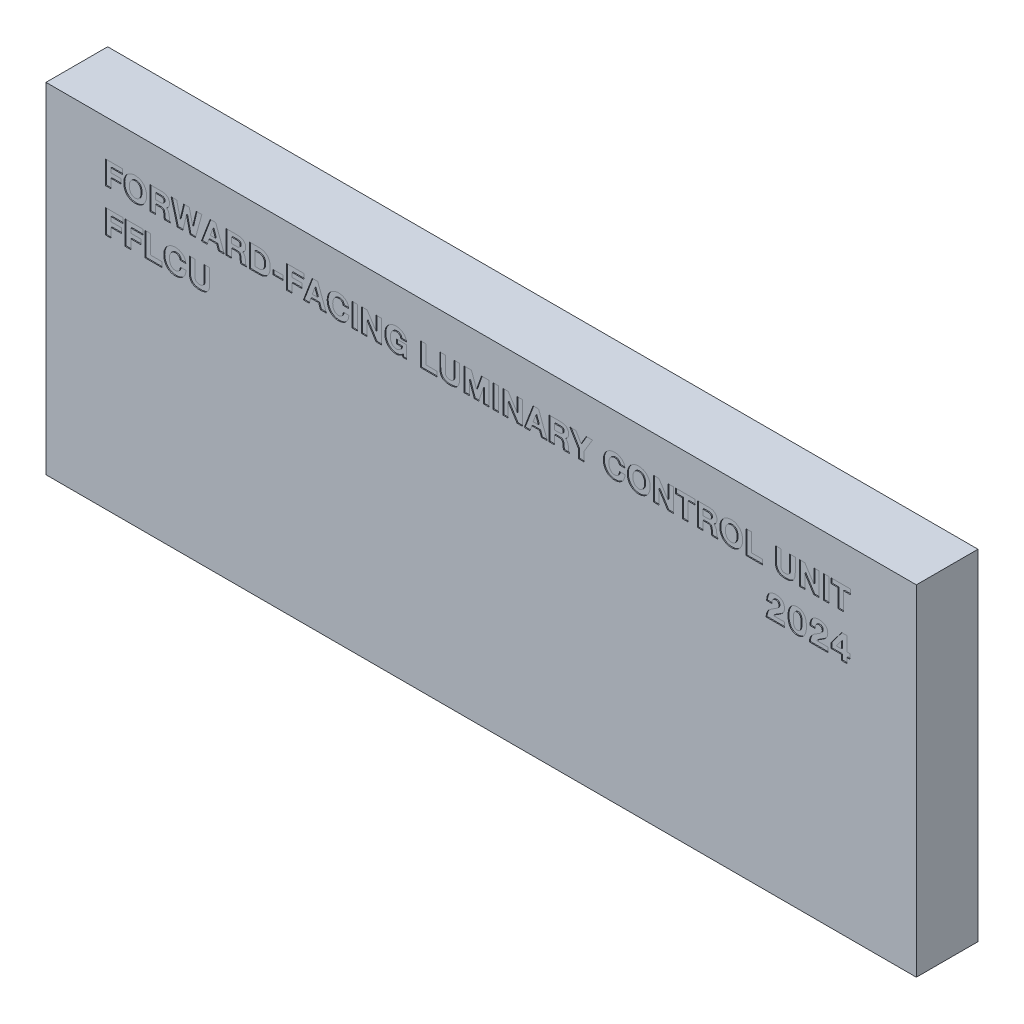
SolidWorks part; units mm, degrees
material "Acrylic (Medium-high impact)"
ref_plane "Front Plane" through (0, 0, 0) normal (0, 0, 1) x (1, 0, 0)
ref_plane "Top Plane" through (0, 0, 0) normal (0, 1, 0) x (1, 0, 0)
ref_plane "Right Plane" through (0, 0, 0) normal (1, 0, 0) x (0, 0, -1)
sketch "Sketch1" plane through (0, 0, 0) normal (0, 0, 1) x (1, 0, 0)
  line L1 (-44.815, -17.5) -> (44.815, -17.5)
  line L2 (-44.815, -17.5) -> (-44.815, 17.5)
  line L3 (-44.815, 17.5) -> (44.815, 17.5)
  line L4 (44.815, -17.5) -> (44.815, 17.5)
  line L5 (-44.815, -17.5) -> (44.815, 17.5) construction
  line L6 (-44.815, 17.5) -> (44.815, -17.5) construction
  point P0 (0, 0)
  dimension "D1" = 89.63
  dimension "D2" = 35
extrude "Boss-Extrude1" add sketch "Sketch1" along normal blind 6.35
sketch "Sketch4" plane through (0, 0, 6.35) normal (0, 0, 1) x (1, 0, 0)
  line L0 (-38.699, 13.734) -> (-36.9131, 13.734)
  line L1 (-36.9131, 13.734) -> (-36.9131, 13.22)
  line L2 (-36.9131, 13.22) -> (-38.1314, 13.22)
  line L3 (-38.1314, 13.22) -> (-38.1314, 12.776)
  line L4 (-38.1314, 12.776) -> (-37.1068, 12.776)
  line L5 (-37.1068, 12.776) -> (-37.1068, 12.282)
  line L6 (-37.1068, 12.282) -> (-38.1314, 12.282)
  line L7 (-38.1314, 12.282) -> (-38.1314, 11.3507)
  line L8 (-38.1314, 11.3507) -> (-38.699, 11.3507)
  line L9 (-38.699, 11.3507) -> (-38.699, 13.734)
  line L10 (-33.5385, 12.6792) -> (-33.0645, 12.6792)
  line L11 (-33.0645, 13.2601) -> (-33.5385, 13.2601)
  line L12 (-33.5385, 13.2601) -> (-33.5385, 12.6792)
  line L13 (-34.1058, 13.734) -> (-32.9343, 13.734)
  line L14 (-32.1265, 11.9215) -> (-32.1097, 11.6978)
  line L15 (-31.9829, 11.3507) -> (-32.6005, 11.3507)
  line L16 (-33.1413, 12.2453) -> (-33.5385, 12.2453)
  line L17 (-33.5385, 12.2453) -> (-33.5385, 11.3507)
  line L18 (-33.5385, 11.3507) -> (-34.1058, 11.3507)
  line L19 (-34.1058, 11.3507) -> (-34.1058, 13.734)
  line L20 (-29.4227, 11.3507) -> (-29.9903, 11.3507)
  line L21 (-29.9903, 11.3507) -> (-30.3441, 12.9196)
  line L22 (-30.3441, 12.9196) -> (-30.3508, 12.9196)
  line L23 (-30.3508, 12.9196) -> (-30.7146, 11.3507)
  line L24 (-30.7146, 11.3507) -> (-31.2955, 11.3507)
  line L25 (-31.2955, 11.3507) -> (-31.9296, 13.734)
  line L26 (-31.9296, 13.734) -> (-31.3487, 13.734)
  line L27 (-31.3487, 13.734) -> (-31.0017, 12.232)
  line L28 (-31.0017, 12.232) -> (-30.9951, 12.232)
  line L29 (-30.9951, 12.232) -> (-30.6279, 13.734)
  line L30 (-30.6279, 13.734) -> (-30.0603, 13.734)
  line L31 (-30.0603, 13.734) -> (-29.7065, 12.232)
  line L32 (-29.7065, 12.232) -> (-29.6998, 12.232)
  line L33 (-29.6998, 12.232) -> (-29.346, 13.734)
  line L34 (-29.346, 13.734) -> (-28.7652, 13.734)
  line L35 (-28.7652, 13.734) -> (-29.4227, 11.3507)
  line L36 (-27.6269, 13.0397) -> (-27.6336, 13.0397)
  line L37 (-27.6336, 13.0397) -> (-27.8941, 12.3154)
  line L38 (-27.8941, 12.3154) -> (-27.3733, 12.3154)
  line L39 (-27.3733, 12.3154) -> (-27.6269, 13.0397)
  line L40 (-27.9107, 13.734) -> (-27.3433, 13.734)
  line L41 (-27.3433, 13.734) -> (-26.4453, 11.3507)
  line L42 (-26.4453, 11.3507) -> (-27.0529, 11.3507)
  line L43 (-27.0529, 11.3507) -> (-27.2364, 11.8814)
  line L44 (-27.2364, 11.8814) -> (-28.0409, 11.8814)
  line L45 (-28.0409, 11.8814) -> (-28.2244, 11.3507)
  line L46 (-28.2244, 11.3507) -> (-28.812, 11.3507)
  line L47 (-28.812, 11.3507) -> (-27.9107, 13.734)
  line L48 (-25.691, 12.6792) -> (-25.217, 12.6792)
  line L49 (-25.217, 13.2601) -> (-25.691, 13.2601)
  line L50 (-25.691, 13.2601) -> (-25.691, 12.6792)
  line L51 (-26.2583, 13.734) -> (-25.0868, 13.734)
  line L52 (-24.279, 11.9215) -> (-24.2622, 11.6978)
  line L53 (-24.1354, 11.3507) -> (-24.753, 11.3507)
  line L54 (-25.2938, 12.2453) -> (-25.691, 12.2453)
  line L55 (-25.691, 12.2453) -> (-25.691, 11.3507)
  line L56 (-25.691, 11.3507) -> (-26.2583, 11.3507)
  line L57 (-26.2583, 11.3507) -> (-26.2583, 13.734)
  line L58 (-23.2811, 11.8447) -> (-22.9138, 11.8447)
  line L59 (-22.9138, 13.24) -> (-23.2811, 13.24)
  line L60 (-23.2811, 13.24) -> (-23.2811, 11.8447)
  line L61 (-23.8484, 13.734) -> (-22.8671, 13.734)
  line L62 (-22.8671, 11.3507) -> (-23.8484, 11.3507)
  line L63 (-23.8484, 11.3507) -> (-23.8484, 13.734)
  line L64 (-21.4484, 12.5056) -> (-20.397, 12.5056)
  line L65 (-20.397, 12.5056) -> (-20.397, 12.0316)
  line L66 (-20.397, 12.0316) -> (-21.4484, 12.0316)
  line L67 (-21.4484, 12.0316) -> (-21.4484, 12.5056)
  line L68 (-20.0332, 13.734) -> (-18.2474, 13.734)
  line L69 (-18.2474, 13.734) -> (-18.2474, 13.22)
  line L70 (-18.2474, 13.22) -> (-19.4657, 13.22)
  line L71 (-19.4657, 13.22) -> (-19.4657, 12.776)
  line L72 (-19.4657, 12.776) -> (-18.441, 12.776)
  line L73 (-18.441, 12.776) -> (-18.441, 12.282)
  line L74 (-18.441, 12.282) -> (-19.4657, 12.282)
  line L75 (-19.4657, 12.282) -> (-19.4657, 11.3507)
  line L76 (-19.4657, 11.3507) -> (-20.0332, 11.3507)
  line L77 (-20.0332, 11.3507) -> (-20.0332, 13.734)
  line L78 (-17.1192, 13.0397) -> (-17.1259, 13.0397)
  line L79 (-17.1259, 13.0397) -> (-17.3863, 12.3154)
  line L80 (-17.3863, 12.3154) -> (-16.8656, 12.3154)
  line L81 (-16.8656, 12.3154) -> (-17.1192, 13.0397)
  line L82 (-17.4029, 13.734) -> (-16.8356, 13.734)
  line L83 (-16.8356, 13.734) -> (-15.9375, 11.3507)
  line L84 (-15.9375, 11.3507) -> (-16.5451, 11.3507)
  line L85 (-16.5451, 11.3507) -> (-16.7287, 11.8814)
  line L86 (-16.7287, 11.8814) -> (-17.5332, 11.8814)
  line L87 (-17.5332, 11.8814) -> (-17.7167, 11.3507)
  line L88 (-17.7167, 11.3507) -> (-18.3042, 11.3507)
  line L89 (-18.3042, 11.3507) -> (-17.4029, 13.734)
  line L90 (-13.6477, 12.9062) -> (-14.2019, 12.9062)
  line L91 (-14.1952, 12.3154) -> (-13.6277, 12.3154)
  line L92 (-13.2939, 13.734) -> (-12.7263, 13.734)
  line L93 (-12.7263, 13.734) -> (-12.7263, 11.3507)
  line L94 (-12.7263, 11.3507) -> (-13.2939, 11.3507)
  line L95 (-13.2939, 11.3507) -> (-13.2939, 13.734)
  line L96 (-12.2993, 13.734) -> (-11.7452, 13.734)
  line L97 (-11.7452, 13.734) -> (-10.8205, 12.3087)
  line L98 (-10.8205, 12.3087) -> (-10.8139, 12.3087)
  line L99 (-10.8139, 12.3087) -> (-10.8139, 13.734)
  line L100 (-10.8139, 13.734) -> (-10.2599, 13.734)
  line L101 (-10.2599, 13.734) -> (-10.2599, 11.3507)
  line L102 (-10.2599, 11.3507) -> (-10.8272, 11.3507)
  line L103 (-10.8272, 11.3507) -> (-11.7385, 12.7926)
  line L104 (-11.7385, 12.7926) -> (-11.7452, 12.7926)
  line L105 (-11.7452, 12.7926) -> (-11.7452, 11.3507)
  line L106 (-11.7452, 11.3507) -> (-12.2993, 11.3507)
  line L107 (-12.2993, 11.3507) -> (-12.2993, 13.734)
  line L108 (-8.7242, 12.6626) -> (-7.6861, 12.6626)
  line L109 (-7.6861, 12.6626) -> (-7.6861, 11.3507)
  line L110 (-7.6861, 11.3507) -> (-8.0633, 11.3507)
  line L111 (-8.0633, 11.3507) -> (-8.1202, 11.571)
  line L112 (-7.7094, 12.9062) -> (-8.2636, 12.9062)
  line L113 (-8.2036, 12.2186) -> (-8.7242, 12.2186)
  line L114 (-8.7242, 12.2186) -> (-8.7242, 12.6626)
  line L115 (-6.2442, 13.734) -> (-5.6767, 13.734)
  line L116 (-5.6767, 13.734) -> (-5.6767, 11.8647)
  line L117 (-5.6767, 11.8647) -> (-4.5418, 11.8647)
  line L118 (-4.5418, 11.8647) -> (-4.5418, 11.3507)
  line L119 (-4.5418, 11.3507) -> (-6.2442, 11.3507)
  line L120 (-6.2442, 11.3507) -> (-6.2442, 13.734)
  line L121 (-4.2649, 13.734) -> (-3.6974, 13.734)
  line L122 (-3.6974, 13.734) -> (-3.6974, 12.3253)
  line L123 (-2.7828, 12.3253) -> (-2.7828, 13.734)
  line L124 (-2.7828, 13.734) -> (-2.2153, 13.734)
  line L125 (-2.2153, 13.734) -> (-2.2153, 12.332)
  line L126 (-4.2649, 12.332) -> (-4.2649, 13.734)
  line L127 (-1.7814, 13.734) -> (-1.0004, 13.734)
  line L128 (-1.0004, 13.734) -> (-0.4831, 12.2887)
  line L129 (-0.4831, 12.2887) -> (-0.4762, 12.2887)
  line L130 (-0.4762, 12.2887) -> (0.0311, 13.734)
  line L131 (0.0311, 13.734) -> (0.7991, 13.734)
  line L132 (0.7991, 13.734) -> (0.7991, 11.3507)
  line L133 (0.7991, 11.3507) -> (0.2316, 11.3507)
  line L134 (0.2316, 11.3507) -> (0.2316, 12.7726)
  line L135 (0.2316, 12.7726) -> (0.2248, 12.7726)
  line L136 (0.2248, 12.7726) -> (-0.2591, 11.3507)
  line L137 (-0.2591, 11.3507) -> (-0.7132, 11.3507)
  line L138 (-0.7132, 11.3507) -> (-1.2072, 12.7726)
  line L139 (-1.2072, 12.7726) -> (-1.2139, 12.7726)
  line L140 (-1.2139, 12.7726) -> (-1.2139, 11.3507)
  line L141 (-1.2139, 11.3507) -> (-1.7814, 11.3507)
  line L142 (-1.7814, 11.3507) -> (-1.7814, 13.734)
  line L143 (1.233, 13.734) -> (1.8005, 13.734)
  line L144 (1.8005, 13.734) -> (1.8005, 11.3507)
  line L145 (1.8005, 11.3507) -> (1.233, 11.3507)
  line L146 (1.233, 11.3507) -> (1.233, 13.734)
  line L147 (2.2279, 13.734) -> (2.7817, 13.734)
  line L148 (2.7817, 13.734) -> (3.7065, 12.3087)
  line L149 (3.7065, 12.3087) -> (3.713, 12.3087)
  line L150 (3.713, 12.3087) -> (3.713, 13.734)
  line L151 (3.713, 13.734) -> (4.2672, 13.734)
  line L152 (4.2672, 13.734) -> (4.2672, 11.3507)
  line L153 (4.2672, 11.3507) -> (3.6996, 11.3507)
  line L154 (3.6996, 11.3507) -> (2.7885, 12.7926)
  line L155 (2.7885, 12.7926) -> (2.7817, 12.7926)
  line L156 (2.7817, 12.7926) -> (2.7817, 11.3507)
  line L157 (2.7817, 11.3507) -> (2.2279, 11.3507)
  line L158 (2.2279, 11.3507) -> (2.2279, 13.734)
  line L159 (5.6288, 13.0397) -> (5.6222, 13.0397)
  line L160 (5.6222, 13.0397) -> (5.3618, 12.3154)
  line L161 (5.3618, 12.3154) -> (5.8827, 12.3154)
  line L162 (5.8827, 12.3154) -> (5.6288, 13.0397)
  line L163 (5.3452, 13.734) -> (5.9127, 13.734)
  line L164 (5.9127, 13.734) -> (6.8104, 11.3507)
  line L165 (6.8104, 11.3507) -> (6.2031, 11.3507)
  line L166 (6.2031, 11.3507) -> (6.0193, 11.8814)
  line L167 (6.0193, 11.8814) -> (5.2151, 11.8814)
  line L168 (5.2151, 11.8814) -> (5.0313, 11.3507)
  line L169 (5.0313, 11.3507) -> (4.4438, 11.3507)
  line L170 (4.4438, 11.3507) -> (5.3452, 13.734)
  line L171 (7.565, 12.6792) -> (8.039, 12.6792)
  line L172 (8.039, 13.2601) -> (7.565, 13.2601)
  line L173 (7.565, 13.2601) -> (7.565, 12.6792)
  line L174 (6.9975, 13.734) -> (8.1694, 13.734)
  line L175 (8.9772, 11.9215) -> (8.9938, 11.6978)
  line L176 (9.1206, 11.3507) -> (8.5032, 11.3507)
  line L177 (7.9624, 12.2453) -> (7.565, 12.2453)
  line L178 (7.565, 12.2453) -> (7.565, 11.3507)
  line L179 (7.565, 11.3507) -> (6.9975, 11.3507)
  line L180 (6.9975, 11.3507) -> (6.9975, 13.734)
  line L181 (10.0085, 12.2686) -> (9.1206, 13.734)
  line L182 (9.1206, 13.734) -> (9.7582, 13.734)
  line L183 (9.7582, 13.734) -> (10.2921, 12.8228)
  line L184 (10.2921, 12.8228) -> (10.8261, 13.734)
  line L185 (10.8261, 13.734) -> (11.4637, 13.734)
  line L186 (11.4637, 13.734) -> (10.5757, 12.2686)
  line L187 (10.5757, 12.2686) -> (10.5757, 11.3507)
  line L188 (10.5757, 11.3507) -> (10.0085, 11.3507)
  line L189 (10.0085, 11.3507) -> (10.0085, 12.2686)
  line L190 (14.7883, 12.9062) -> (14.2341, 12.9062)
  line L191 (14.2407, 12.3154) -> (14.8082, 12.3154)
  line L192 (17.7459, 13.734) -> (18.2997, 13.734)
  line L193 (18.2997, 13.734) -> (19.2245, 12.3087)
  line L194 (19.2245, 12.3087) -> (19.231, 12.3087)
  line L195 (19.231, 12.3087) -> (19.231, 13.734)
  line L196 (19.231, 13.734) -> (19.7852, 13.734)
  line L197 (19.7852, 13.734) -> (19.7852, 11.3507)
  line L198 (19.7852, 11.3507) -> (19.2176, 11.3507)
  line L199 (19.2176, 11.3507) -> (18.3065, 12.7926)
  line L200 (18.3065, 12.7926) -> (18.2997, 12.7926)
  line L201 (18.2997, 12.7926) -> (18.2997, 11.3507)
  line L202 (18.2997, 11.3507) -> (17.7459, 11.3507)
  line L203 (17.7459, 11.3507) -> (17.7459, 13.734)
  line L204 (20.7399, 13.22) -> (20.0221, 13.22)
  line L205 (20.0221, 13.22) -> (20.0221, 13.734)
  line L206 (20.0221, 13.734) -> (22.0249, 13.734)
  line L207 (22.0249, 13.734) -> (22.0249, 13.22)
  line L208 (22.0249, 13.22) -> (21.3075, 13.22)
  line L209 (21.3075, 13.22) -> (21.3075, 11.3507)
  line L210 (21.3075, 11.3507) -> (20.7399, 11.3507)
  line L211 (20.7399, 11.3507) -> (20.7399, 13.22)
  line L212 (22.8395, 12.6792) -> (23.3135, 12.6792)
  line L213 (23.3135, 13.2601) -> (22.8395, 13.2601)
  line L214 (22.8395, 13.2601) -> (22.8395, 12.6792)
  line L215 (22.272, 13.734) -> (23.4439, 13.734)
  line L216 (24.2517, 11.9215) -> (24.2683, 11.6978)
  line L217 (24.3951, 11.3507) -> (23.7777, 11.3507)
  line L218 (23.2369, 12.2453) -> (22.8395, 12.2453)
  line L219 (22.8395, 12.2453) -> (22.8395, 11.3507)
  line L220 (22.8395, 11.3507) -> (22.272, 11.3507)
  line L221 (22.272, 11.3507) -> (22.272, 13.734)
  line L222 (27.262, 13.734) -> (27.8295, 13.734)
  line L223 (27.8295, 13.734) -> (27.8295, 11.8647)
  line L224 (27.8295, 11.8647) -> (28.9646, 11.8647)
  line L225 (28.9646, 11.8647) -> (28.9646, 11.3507)
  line L226 (28.9646, 11.3507) -> (27.262, 11.3507)
  line L227 (27.262, 11.3507) -> (27.262, 13.734)
  line L228 (30.2962, 13.734) -> (30.8637, 13.734)
  line L229 (30.8637, 13.734) -> (30.8637, 12.3253)
  line L230 (31.7784, 12.3253) -> (31.7784, 13.734)
  line L231 (31.7784, 13.734) -> (32.3456, 13.734)
  line L232 (32.3456, 13.734) -> (32.3456, 12.332)
  line L233 (30.2962, 12.332) -> (30.2962, 13.734)
  line L234 (32.7733, 13.734) -> (33.3271, 13.734)
  line L235 (33.3271, 13.734) -> (34.2519, 12.3087)
  line L236 (34.2519, 12.3087) -> (34.2584, 12.3087)
  line L237 (34.2584, 12.3087) -> (34.2584, 13.734)
  line L238 (34.2584, 13.734) -> (34.8126, 13.734)
  line L239 (34.8126, 13.734) -> (34.8126, 11.3507)
  line L240 (34.8126, 11.3507) -> (34.245, 11.3507)
  line L241 (34.245, 11.3507) -> (33.3339, 12.7926)
  line L242 (33.3339, 12.7926) -> (33.3271, 12.7926)
  line L243 (33.3271, 12.7926) -> (33.3271, 11.3507)
  line L244 (33.3271, 11.3507) -> (32.7733, 11.3507)
  line L245 (32.7733, 11.3507) -> (32.7733, 13.734)
  line L246 (35.2399, 13.734) -> (35.8074, 13.734)
  line L247 (35.8074, 13.734) -> (35.8074, 11.3507)
  line L248 (35.8074, 11.3507) -> (35.2399, 11.3507)
  line L249 (35.2399, 11.3507) -> (35.2399, 13.734)
  line L250 (36.7554, 13.22) -> (36.0376, 13.22)
  line L251 (36.0376, 13.22) -> (36.0376, 13.734)
  line L252 (36.0376, 13.734) -> (38.0404, 13.734)
  line L253 (38.0404, 13.734) -> (38.0404, 13.22)
  line L254 (38.0404, 13.22) -> (37.3229, 13.22)
  line L255 (37.3229, 13.22) -> (37.3229, 11.3507)
  line L256 (37.3229, 11.3507) -> (36.7554, 11.3507)
  line L257 (36.7554, 11.3507) -> (36.7554, 13.22)
  line L258 (-38.697, 9.3966) -> (-36.8627, 9.3966)
  line L259 (-36.8627, 9.3966) -> (-36.8627, 8.8685)
  line L260 (-36.8627, 8.8685) -> (-38.1138, 8.8685)
  line L261 (-38.1138, 8.8685) -> (-38.1138, 8.4126)
  line L262 (-38.1138, 8.4126) -> (-37.0614, 8.4126)
  line L263 (-37.0614, 8.4126) -> (-37.0614, 7.905)
  line L264 (-37.0614, 7.905) -> (-38.1138, 7.905)
  line L265 (-38.1138, 7.905) -> (-38.1138, 6.9486)
  line L266 (-38.1138, 6.9486) -> (-38.697, 6.9486)
  line L267 (-38.697, 6.9486) -> (-38.697, 9.3966)
  line L268 (-36.6641, 9.3966) -> (-34.8299, 9.3966)
  line L269 (-34.8299, 9.3966) -> (-34.8299, 8.8685)
  line L270 (-34.8299, 8.8685) -> (-36.081, 8.8685)
  line L271 (-36.081, 8.8685) -> (-36.081, 8.4126)
  line L272 (-36.081, 8.4126) -> (-35.0285, 8.4126)
  line L273 (-35.0285, 8.4126) -> (-35.0285, 7.905)
  line L274 (-35.0285, 7.905) -> (-36.081, 7.905)
  line L275 (-36.081, 7.905) -> (-36.081, 6.9486)
  line L276 (-36.081, 6.9486) -> (-36.6641, 6.9486)
  line L277 (-36.6641, 6.9486) -> (-36.6641, 9.3966)
  line L278 (-34.6307, 9.3966) -> (-34.0475, 9.3966)
  line L279 (-34.0475, 9.3966) -> (-34.0475, 7.4765)
  line L280 (-34.0475, 7.4765) -> (-32.8818, 7.4765)
  line L281 (-32.8818, 7.4765) -> (-32.8818, 6.9486)
  line L282 (-32.8818, 6.9486) -> (-34.6307, 6.9486)
  line L283 (-34.6307, 6.9486) -> (-34.6307, 9.3966)
  line L284 (-30.4204, 8.5462) -> (-30.9895, 8.5462)
  line L285 (-30.9828, 7.9394) -> (-30.4003, 7.9394)
  line L286 (-30.0571, 9.3966) -> (-29.4739, 9.3966)
  line L287 (-29.4739, 9.3966) -> (-29.4739, 7.9497)
  line L288 (-28.5348, 7.9497) -> (-28.5348, 9.3966)
  line L289 (-28.5348, 9.3966) -> (-27.9522, 9.3966)
  line L290 (-27.9522, 9.3966) -> (-27.9522, 7.9567)
  line L291 (-30.0571, 7.9567) -> (-30.0571, 9.3966)
  line L292 (30.7116, 7.8314) -> (30.2989, 7.5702)
  line L293 (30.1013, 7.4009) -> (31.2442, 7.4009)
  line L294 (31.2442, 7.4009) -> (31.2442, 6.9)
  line L295 (31.2442, 6.9) -> (29.35, 6.9)
  line L296 (29.9284, 7.8984) -> (30.3871, 8.1912)
  line L297 (29.9355, 8.3922) -> (29.4063, 8.3922)
  line L298 (29.4063, 8.3922) -> (29.4063, 8.4699)
  line L299 (35.1706, 7.8314) -> (34.7579, 7.5702)
  line L300 (34.5603, 7.4009) -> (35.7032, 7.4009)
  line L301 (35.7032, 7.4009) -> (35.7032, 6.9)
  line L302 (35.7032, 6.9) -> (33.8089, 6.9)
  line L303 (34.3874, 7.8984) -> (34.8461, 8.1912)
  line L304 (34.3944, 8.3922) -> (33.8653, 8.3922)
  line L305 (33.8653, 8.3922) -> (33.8653, 8.4699)
  line L306 (37.1002, 7.9371) -> (37.1002, 8.6286)
  line L307 (37.1002, 8.6286) -> (37.0932, 8.6286)
  line L308 (37.0932, 8.6286) -> (36.5852, 7.9371)
  line L309 (36.5852, 7.9371) -> (37.1002, 7.9371)
  line L310 (36.0384, 7.9688) -> (37.1285, 9.3977)
  line L311 (37.1285, 9.3977) -> (37.6647, 9.3977)
  line L312 (37.6647, 9.3977) -> (37.6647, 7.9371)
  line L313 (37.6647, 7.9371) -> (37.9787, 7.9371)
  line L314 (37.9787, 7.9371) -> (37.9787, 7.4362)
  line L315 (37.9787, 7.4362) -> (37.6647, 7.4362)
  line L316 (37.6647, 7.4362) -> (37.6647, 6.9)
  line L317 (37.6647, 6.9) -> (37.1002, 6.9)
  line L318 (37.1002, 6.9) -> (37.1002, 7.4362)
  line L319 (37.1002, 7.4362) -> (36.0384, 7.4362)
  line L320 (36.0384, 7.4362) -> (36.0384, 7.9688)
  spline S0 degree 3 poles (-36.0403, 11.9431) (-35.9813, 11.882) (-35.9163, 11.838) (-35.7738, 11.7846) (-35.7026, 11.7712) (-35.6314, 11.7712) knots 14 14 14 14 15 15 16 16 16 16
  spline S1 degree 3 poles (-36.1839, 12.1819) (-36.1471, 12.084) (-36.0993, 12.0044) (-36.0403, 11.9431) knots 13 13 13 13 14 14 14 14
  spline S2 degree 3 poles (-36.1839, 12.9028) (-36.2206, 12.8049) (-36.239, 12.6847) (-36.239, 12.3998) (-36.2206, 12.2797) (-36.1839, 12.1819) knots 11 11 11 11 12 12 13 13 13 13
  spline S3 degree 3 poles (-36.0403, 13.1416) (-36.0993, 13.0803) (-36.1471, 13.0008) (-36.1839, 12.9028) knots 10 10 10 10 11 11 11 11
  spline S4 degree 3 poles (-35.8451, 13.2733) (-35.9163, 13.2467) (-35.9813, 13.2027) (-36.0403, 13.1416) knots 9 9 9 9 10 10 10 10
  spline S5 degree 3 poles (-35.4195, 13.2733) (-35.4919, 13.3) (-35.5624, 13.3134) (-35.6314, 13.3134) (-35.7026, 13.3134) (-35.7738, 13.3) (-35.8451, 13.2733) knots 7 7 7 7 8 8 8 9 9 9 9
  spline S6 degree 3 poles (-35.2225, 13.1416) (-35.2815, 13.2027) (-35.3471, 13.2467) (-35.4195, 13.2733) knots 6 6 6 6 7 7 7 7
  spline S7 degree 3 poles (-35.079, 12.1819) (-35.0424, 12.2797) (-35.0239, 12.3998) (-35.0239, 12.6847) (-35.0424, 12.8049) (-35.1157, 13.0008) (-35.1636, 13.0803) (-35.2225, 13.1416) knots 3 3 3 3 4 4 5 5 6 6 6 6
  spline S8 degree 3 poles (-35.2225, 11.9431) (-35.1636, 12.0044) (-35.1157, 12.084) (-35.079, 12.1819) knots 2 2 2 2 3 3 3 3
  spline S9 degree 3 poles (-35.6314, 11.7712) (-35.5624, 11.7712) (-35.4919, 11.7846) (-35.3471, 11.838) (-35.2815, 11.882) (-35.2225, 11.9431) knots 0 0 0 0 1 1 2 2 2 2
  spline S10 degree 3 poles (-36.1005, 13.699) (-35.9569, 13.7578) (-35.8006, 13.7873) (-35.6314, 13.7873) knots 15 15 15 15 16 16 16 16
  spline S11 degree 3 poles (-36.4726, 13.4487) (-36.3681, 13.5565) (-36.2439, 13.64) (-36.1005, 13.699) knots 14 14 14 14 15 15 15 15
  spline S12 degree 3 poles (-36.718, 13.0563) (-36.659, 13.2099) (-36.5772, 13.3406) (-36.4726, 13.4487) knots 13 13 13 13 14 14 14 14
  spline S13 degree 3 poles (-36.718, 12.0282) (-36.7769, 12.1819) (-36.8064, 12.3532) (-36.8064, 12.5423) (-36.8064, 12.7315) (-36.7769, 12.9028) (-36.718, 13.0563) knots 11 11 11 11 12 12 12 13 13 13 13
  spline S14 degree 3 poles (-36.4726, 11.6361) (-36.5772, 11.744) (-36.659, 11.8747) (-36.718, 12.0282) knots 10 10 10 10 11 11 11 11
  spline S15 degree 3 poles (-36.1005, 11.3857) (-36.2439, 11.4447) (-36.3681, 11.5282) (-36.4726, 11.6361) knots 9 9 9 9 10 10 10 10
  spline S16 degree 3 poles (-35.1625, 11.3857) (-35.3059, 11.3267) (-35.4624, 11.2972) (-35.6314, 11.2972) (-35.8006, 11.2972) (-35.9569, 11.3267) (-36.1005, 11.3857) knots 7 7 7 7 8 8 8 9 9 9 9
  spline S17 degree 3 poles (-34.7902, 11.6361) (-34.8949, 11.5282) (-35.0189, 11.4447) (-35.1625, 11.3857) knots 6 6 6 6 7 7 7 7
  spline S18 degree 3 poles (-34.5449, 12.0282) (-34.6039, 11.8747) (-34.6857, 11.744) (-34.7902, 11.6361) knots 5 5 5 5 6 6 6 6
  spline S19 degree 3 poles (-34.7902, 13.4487) (-34.6857, 13.3406) (-34.6039, 13.2099) (-34.4859, 12.9028) (-34.4564, 12.7315) (-34.4564, 12.5423) (-34.4564, 12.3532) (-34.4859, 12.1819) (-34.5449, 12.0282) knots 2 2 2 2 3 3 4 4 4 5 5 5 5
  spline S20 degree 3 poles (-35.1625, 13.699) (-35.0189, 13.64) (-34.8949, 13.5565) (-34.7902, 13.4487) knots 1 1 1 1 2 2 2 2
  spline S21 degree 3 poles (-35.6314, 13.7873) (-35.4624, 13.7873) (-35.3059, 13.7578) (-35.1625, 13.699) knots 0 0 0 0 1 1 1 1
  spline S22 degree 3 poles (-33.0645, 12.6792) (-33.0267, 12.6792) (-32.9843, 12.6808) (-32.9375, 12.6842) knots 1 1 1 1 2 2 2 2
  spline S23 degree 3 poles (-32.9375, 12.6842) (-32.8909, 12.6875) (-32.8474, 12.6981) (-32.8075, 12.7159) knots 2 2 2 2 3 3 3 3
  spline S24 degree 3 poles (-32.8075, 12.7159) (-32.7674, 12.7336) (-32.734, 12.7626) (-32.7072, 12.8027) knots 3 3 3 3 4 4 4 4
  spline S25 degree 3 poles (-32.7072, 12.8027) (-32.6805, 12.8428) (-32.6671, 12.8995) (-32.6671, 12.9729) knots 4 4 4 4 5 5 5 5
  spline S26 degree 3 poles (-32.6671, 12.9729) (-32.6671, 13.0441) (-32.6805, 13.0992) (-32.7072, 13.1382) knots 5 5 5 5 6 6 6 6
  spline S27 degree 3 poles (-32.7072, 13.1382) (-32.734, 13.1771) (-32.7674, 13.2055) (-32.8075, 13.2232) knots 6 6 6 6 7 7 7 7
  spline S28 degree 3 poles (-32.8075, 13.2232) (-32.8474, 13.241) (-32.8909, 13.2516) (-32.9375, 13.255) knots 7 7 7 7 8 8 8 8
  spline S29 degree 3 poles (-32.9375, 13.255) (-32.9843, 13.2583) (-33.0267, 13.2601) (-33.0645, 13.2601) knots 8 8 8 8 9 9 9 9
  spline S30 degree 3 poles (-32.9343, 13.734) (-32.8275, 13.734) (-32.724, 13.7228) (-32.6238, 13.7006) knots 1 1 1 1 2 2 2 2
  spline S31 degree 3 poles (-32.6238, 13.7006) (-32.5237, 13.6783) (-32.4347, 13.641) (-32.3568, 13.5888) knots 2 2 2 2 3 3 3 3
  spline S32 degree 3 poles (-32.3568, 13.5888) (-32.2789, 13.5365) (-32.2167, 13.4669) (-32.1699, 13.3802) knots 3 3 3 3 4 4 4 4
  spline S33 degree 3 poles (-32.1699, 13.3802) (-32.1231, 13.2933) (-32.0998, 13.1854) (-32.0998, 13.0563) knots 4 4 4 4 5 5 5 5
  spline S34 degree 3 poles (-32.0998, 13.0563) (-32.0998, 12.9718) (-32.1104, 12.8973) (-32.1314, 12.8327) knots 5 5 5 5 6 6 6 6
  spline S35 degree 3 poles (-32.1314, 12.8327) (-32.1526, 12.7682) (-32.1788, 12.7131) (-32.21, 12.6675) knots 6 6 6 6 7 7 7 7
  spline S36 degree 3 poles (-32.21, 12.6675) (-32.2411, 12.6218) (-32.275, 12.5835) (-32.3117, 12.5524) knots 7 7 7 7 8 8 8 8
  spline S37 degree 3 poles (-32.3117, 12.5524) (-32.3485, 12.5211) (-32.3824, 12.4966) (-32.4135, 12.4789) knots 8 8 8 8 9 9 9 9
  spline S38 degree 3 poles (-32.4135, 12.4789) (-32.3068, 12.421) (-32.2339, 12.3426) (-32.195, 12.2435) knots 9 9 9 9 10 10 10 10
  spline S39 degree 3 poles (-32.195, 12.2435) (-32.156, 12.1446) (-32.1332, 12.0372) (-32.1265, 11.9215) knots 10 10 10 10 11 11 11 11
  spline S40 degree 3 poles (-32.1097, 11.6978) (-32.1053, 11.6377) (-32.0986, 11.5882) (-32.0897, 11.5494) knots 12 12 12 12 13 13 13 13
  spline S41 degree 3 poles (-32.0897, 11.5494) (-32.0809, 11.5104) (-32.0703, 11.478) (-32.0581, 11.4525) knots 13 13 13 13 14 14 14 14
  spline S42 degree 3 poles (-32.0581, 11.4525) (-32.0458, 11.427) (-32.033, 11.4063) (-32.0196, 11.3908) knots 14 14 14 14 15 15 15 15
  spline S43 degree 3 poles (-32.0196, 11.3908) (-32.0062, 11.3751) (-31.9942, 11.3618) (-31.9829, 11.3507) knots 15 15 15 15 16 16 16 16
  spline S44 degree 3 poles (-32.6005, 11.3507) (-32.6183, 11.364) (-32.6328, 11.4035) (-32.6438, 11.4692) knots 17 17 17 17 18 18 18 18
  spline S45 degree 3 poles (-32.6438, 11.4692) (-32.6551, 11.5349) (-32.665, 11.6322) (-32.6738, 11.7612) knots 18 18 18 18 19 19 19 19
  spline S46 degree 3 poles (-32.6738, 11.7612) (-32.6805, 11.868) (-32.6929, 11.9532) (-32.7107, 12.0166) knots 19 19 19 19 20 20 20 20
  spline S47 degree 3 poles (-32.7107, 12.0166) (-32.7284, 12.08) (-32.7552, 12.1289) (-32.7907, 12.1635) knots 20 20 20 20 21 21 21 21
  spline S48 degree 3 poles (-32.7907, 12.1635) (-32.8264, 12.1979) (-32.8725, 12.2202) (-32.9292, 12.2302) knots 21 21 21 21 22 22 22 22
  spline S49 degree 3 poles (-32.9292, 12.2302) (-32.986, 12.2403) (-33.0567, 12.2453) (-33.1413, 12.2453) knots 22 22 22 22 23 23 23 23
  spline S50 degree 3 poles (-25.217, 12.6792) (-25.1792, 12.6792) (-25.1368, 12.6808) (-25.09, 12.6842) knots 1 1 1 1 2 2 2 2
  spline S51 degree 3 poles (-25.09, 12.6842) (-25.0434, 12.6875) (-24.9999, 12.6981) (-24.96, 12.7159) knots 2 2 2 2 3 3 3 3
  spline S52 degree 3 poles (-24.96, 12.7159) (-24.9199, 12.7336) (-24.8865, 12.7626) (-24.8597, 12.8027) knots 3 3 3 3 4 4 4 4
  spline S53 degree 3 poles (-24.8597, 12.8027) (-24.833, 12.8428) (-24.8197, 12.8995) (-24.8197, 12.9729) knots 4 4 4 4 5 5 5 5
  spline S54 degree 3 poles (-24.8197, 12.9729) (-24.8197, 13.0441) (-24.833, 13.0992) (-24.8597, 13.1382) knots 5 5 5 5 6 6 6 6
  spline S55 degree 3 poles (-24.8597, 13.1382) (-24.8865, 13.1771) (-24.9199, 13.2055) (-24.96, 13.2232) knots 6 6 6 6 7 7 7 7
  spline S56 degree 3 poles (-24.96, 13.2232) (-24.9999, 13.241) (-25.0434, 13.2516) (-25.09, 13.255) knots 7 7 7 7 8 8 8 8
  spline S57 degree 3 poles (-25.09, 13.255) (-25.1368, 13.2583) (-25.1792, 13.2601) (-25.217, 13.2601) knots 8 8 8 8 9 9 9 9
  spline S58 degree 3 poles (-25.0868, 13.734) (-24.98, 13.734) (-24.8765, 13.7228) (-24.7763, 13.7006) knots 1 1 1 1 2 2 2 2
  spline S59 degree 3 poles (-24.7763, 13.7006) (-24.6762, 13.6783) (-24.5872, 13.641) (-24.5093, 13.5888) knots 2 2 2 2 3 3 3 3
  spline S60 degree 3 poles (-24.5093, 13.5888) (-24.4314, 13.5365) (-24.3692, 13.4669) (-24.3224, 13.3802) knots 3 3 3 3 4 4 4 4
  spline S61 degree 3 poles (-24.3224, 13.3802) (-24.2756, 13.2933) (-24.2523, 13.1854) (-24.2523, 13.0563) knots 4 4 4 4 5 5 5 5
  spline S62 degree 3 poles (-24.2523, 13.0563) (-24.2523, 12.9718) (-24.2629, 12.8973) (-24.2839, 12.8327) knots 5 5 5 5 6 6 6 6
  spline S63 degree 3 poles (-24.2839, 12.8327) (-24.3051, 12.7682) (-24.3313, 12.7131) (-24.3625, 12.6675) knots 6 6 6 6 7 7 7 7
  spline S64 degree 3 poles (-24.3625, 12.6675) (-24.3936, 12.6218) (-24.4275, 12.5835) (-24.4642, 12.5524) knots 7 7 7 7 8 8 8 8
  spline S65 degree 3 poles (-24.4642, 12.5524) (-24.501, 12.5211) (-24.5349, 12.4966) (-24.566, 12.4789) knots 8 8 8 8 9 9 9 9
  spline S66 degree 3 poles (-24.566, 12.4789) (-24.4593, 12.421) (-24.3864, 12.3426) (-24.3475, 12.2435) knots 9 9 9 9 10 10 10 10
  spline S67 degree 3 poles (-24.3475, 12.2435) (-24.3085, 12.1446) (-24.2857, 12.0372) (-24.279, 11.9215) knots 10 10 10 10 11 11 11 11
  spline S68 degree 3 poles (-24.2622, 11.6978) (-24.2578, 11.6377) (-24.2512, 11.5882) (-24.2422, 11.5494) knots 12 12 12 12 13 13 13 13
  spline S69 degree 3 poles (-24.2422, 11.5494) (-24.2334, 11.5104) (-24.2228, 11.478) (-24.2106, 11.4525) knots 13 13 13 13 14 14 14 14
  spline S70 degree 3 poles (-24.2106, 11.4525) (-24.1983, 11.427) (-24.1855, 11.4063) (-24.1721, 11.3908) knots 14 14 14 14 15 15 15 15
  spline S71 degree 3 poles (-24.1721, 11.3908) (-24.1587, 11.3751) (-24.1467, 11.3618) (-24.1354, 11.3507) knots 15 15 15 15 16 16 16 16
  spline S72 degree 3 poles (-24.753, 11.3507) (-24.7708, 11.364) (-24.7853, 11.4035) (-24.7963, 11.4692) knots 17 17 17 17 18 18 18 18
  spline S73 degree 3 poles (-24.7963, 11.4692) (-24.8076, 11.5349) (-24.8175, 11.6322) (-24.8263, 11.7612) knots 18 18 18 18 19 19 19 19
  spline S74 degree 3 poles (-24.8263, 11.7612) (-24.833, 11.868) (-24.8454, 11.9532) (-24.8632, 12.0166) knots 19 19 19 19 20 20 20 20
  spline S75 degree 3 poles (-24.8632, 12.0166) (-24.8809, 12.08) (-24.9077, 12.1289) (-24.9432, 12.1635) knots 20 20 20 20 21 21 21 21
  spline S76 degree 3 poles (-24.9432, 12.1635) (-24.9789, 12.1979) (-25.025, 12.2202) (-25.0817, 12.2302) knots 21 21 21 21 22 22 22 22
  spline S77 degree 3 poles (-25.0817, 12.2302) (-25.1385, 12.2403) (-25.2092, 12.2453) (-25.2938, 12.2453) knots 22 22 22 22 23 23 23 23
  spline S78 degree 3 poles (-22.9138, 11.8447) (-22.8938, 11.8447) (-22.8643, 11.8458) (-22.8253, 11.8481) knots 1 1 1 1 2 2 2 2
  spline S79 degree 3 poles (-22.8253, 11.8481) (-22.7866, 11.8502) (-22.7442, 11.8581) (-22.6985, 11.8714) knots 2 2 2 2 3 3 3 3
  spline S80 degree 3 poles (-22.6985, 11.8714) (-22.6529, 11.8848) (-22.6063, 11.9053) (-22.5584, 11.9332) knots 3 3 3 3 4 4 4 4
  spline S81 degree 3 poles (-22.5584, 11.9332) (-22.5105, 11.9609) (-22.4671, 12.0005) (-22.4281, 12.0517) knots 4 4 4 4 5 5 5 5
  spline S82 degree 3 poles (-22.4281, 12.0517) (-22.3892, 12.1029) (-22.3569, 12.1686) (-22.3313, 12.2486) knots 5 5 5 5 6 6 6 6
  spline S83 degree 3 poles (-22.3313, 12.2486) (-22.3057, 12.3288) (-22.293, 12.4266) (-22.293, 12.5423) knots 6 6 6 6 7 7 7 7
  spline S84 degree 3 poles (-22.293, 12.5423) (-22.293, 12.658) (-22.3057, 12.756) (-22.3313, 12.8361) knots 7 7 7 7 8 8 8 8
  spline S85 degree 3 poles (-22.3313, 12.8361) (-22.3569, 12.9162) (-22.3892, 12.9819) (-22.4281, 13.033) knots 8 8 8 8 9 9 9 9
  spline S86 degree 3 poles (-22.4281, 13.033) (-22.4671, 13.0842) (-22.5105, 13.1237) (-22.5584, 13.1515) knots 9 9 9 9 10 10 10 10
  spline S87 degree 3 poles (-22.5584, 13.1515) (-22.6063, 13.1794) (-22.6529, 13.1999) (-22.6985, 13.2133) knots 10 10 10 10 11 11 11 11
  spline S88 degree 3 poles (-22.6985, 13.2133) (-22.7442, 13.2267) (-22.7866, 13.2343) (-22.8253, 13.2366) knots 11 11 11 11 12 12 12 12
  spline S89 degree 3 poles (-22.8253, 13.2366) (-22.8643, 13.2389) (-22.8938, 13.24) (-22.9138, 13.24) knots 12 12 12 12 13 13 13 13
  spline S90 degree 3 poles (-22.8671, 13.734) (-22.7002, 13.734) (-22.5466, 13.7101) (-22.4065, 13.6622) knots 1 1 1 1 2 2 2 2
  spline S91 degree 3 poles (-22.4065, 13.6622) (-22.2663, 13.6144) (-22.1462, 13.5416) (-22.0459, 13.4436) knots 2 2 2 2 3 3 3 3
  spline S92 degree 3 poles (-22.0459, 13.4436) (-21.9459, 13.3456) (-21.8673, 13.2216) (-21.8106, 13.0713) knots 3 3 3 3 4 4 4 4
  spline S93 degree 3 poles (-21.8106, 13.0713) (-21.7539, 12.9212) (-21.7255, 12.7449) (-21.7255, 12.5423) knots 4 4 4 4 5 5 5 5
  spline S94 degree 3 poles (-21.7255, 12.5423) (-21.7255, 12.3376) (-21.7539, 12.1607) (-21.8106, 12.0116) knots 5 5 5 5 6 6 6 6
  spline S95 degree 3 poles (-21.8106, 12.0116) (-21.8673, 11.8625) (-21.9459, 11.7389) (-22.0459, 11.6411) knots 6 6 6 6 7 7 7 7
  spline S96 degree 3 poles (-22.0459, 11.6411) (-22.1462, 11.5432) (-22.2663, 11.4703) (-22.4065, 11.4224) knots 7 7 7 7 8 8 8 8
  spline S97 degree 3 poles (-22.4065, 11.4224) (-22.5466, 11.3746) (-22.7002, 11.3507) (-22.8671, 11.3507) knots 8 8 8 8 9 9 9 9
  spline S98 degree 3 poles (-13.6277, 12.3154) (-13.6277, 12.253) (-13.635, 12.1845) (-13.6493, 12.11) knots 0 0 0 0 1 1 1 1
  spline S99 degree 3 poles (-13.6493, 12.11) (-13.6638, 12.0356) (-13.6878, 11.9604) (-13.7212, 11.8848) knots 1 1 1 1 2 2 2 2
  spline S100 degree 3 poles (-13.7212, 11.8848) (-13.7545, 11.809) (-13.7985, 11.7361) (-13.8529, 11.6661) knots 2 2 2 2 3 3 3 3
  spline S101 degree 3 poles (-13.8529, 11.6661) (-13.9075, 11.596) (-13.9748, 11.5337) (-14.055, 11.4791) knots 3 3 3 3 4 4 4 4
  spline S102 degree 3 poles (-14.055, 11.4791) (-14.135, 11.4247) (-14.2284, 11.3807) (-14.3354, 11.3474) knots 4 4 4 4 5 5 5 5
  spline S103 degree 3 poles (-14.3354, 11.3474) (-14.4421, 11.314) (-14.5645, 11.2972) (-14.7026, 11.2972) knots 5 5 5 5 6 6 6 6
  spline S104 degree 3 poles (-14.7026, 11.2972) (-14.8649, 11.2972) (-15.0163, 11.3267) (-15.1565, 11.3857) knots 6 6 6 6 7 7 7 7
  spline S105 degree 3 poles (-15.1565, 11.3857) (-15.2966, 11.4447) (-15.4186, 11.5282) (-15.5219, 11.6361) knots 7 7 7 7 8 8 8 8
  spline S106 degree 3 poles (-15.5219, 11.6361) (-15.6254, 11.744) (-15.7067, 11.8747) (-15.7657, 12.0282) knots 8 8 8 8 9 9 9 9
  spline S107 degree 3 poles (-15.7657, 12.0282) (-15.8246, 12.1819) (-15.8541, 12.3532) (-15.8541, 12.5423) knots 9 9 9 9 10 10 10 10
  spline S108 degree 3 poles (-15.8541, 12.5423) (-15.8541, 12.7315) (-15.8246, 12.9028) (-15.7657, 13.0563) knots 10 10 10 10 11 11 11 11
  spline S109 degree 3 poles (-15.7657, 13.0563) (-15.7067, 13.2099) (-15.6249, 13.3406) (-15.5203, 13.4487) knots 11 11 11 11 12 12 12 12
  spline S110 degree 3 poles (-15.5203, 13.4487) (-15.4158, 13.5565) (-15.2916, 13.64) (-15.1482, 13.699) knots 12 12 12 12 13 13 13 13
  spline S111 degree 3 poles (-15.1482, 13.699) (-15.0046, 13.7578) (-14.8483, 13.7873) (-14.6791, 13.7873) knots 13 13 13 13 14 14 14 14
  spline S112 degree 3 poles (-14.6791, 13.7873) (-14.5479, 13.7873) (-14.4199, 13.7657) (-14.2953, 13.7223) knots 14 14 14 14 15 15 15 15
  spline S113 degree 3 poles (-14.2953, 13.7223) (-14.1707, 13.679) (-14.0606, 13.6183) (-13.9649, 13.5404) knots 15 15 15 15 16 16 16 16
  spline S114 degree 3 poles (-13.9649, 13.5404) (-13.8692, 13.4625) (-13.7924, 13.3696) (-13.7344, 13.2617) knots 16 16 16 16 17 17 17 17
  spline S115 degree 3 poles (-13.7344, 13.2617) (-13.6767, 13.1536) (-13.6477, 13.0352) (-13.6477, 12.9062) knots 17 17 17 17 18 18 18 18
  spline S116 degree 3 poles (-14.2019, 12.9062) (-14.2263, 13.0374) (-14.2798, 13.1382) (-14.3621, 13.2082) knots 19 19 19 19 20 20 20 20
  spline S117 degree 3 poles (-14.3621, 13.2082) (-14.4444, 13.2783) (-14.5502, 13.3134) (-14.6791, 13.3134) knots 20 20 20 20 21 21 21 21
  spline S118 degree 3 poles (-14.6791, 13.3134) (-14.7503, 13.3134) (-14.8215, 13.3) (-14.8928, 13.2733) knots 21 21 21 21 22 22 22 22
  spline S119 degree 3 poles (-14.8928, 13.2733) (-14.964, 13.2467) (-15.029, 13.2027) (-15.088, 13.1416) knots 22 22 22 22 23 23 23 23
  spline S120 degree 3 poles (-15.088, 13.1416) (-15.147, 13.0803) (-15.1948, 13.0008) (-15.2316, 12.9028) knots 23 23 23 23 24 24 24 24
  spline S121 degree 3 poles (-15.2316, 12.9028) (-15.2683, 12.8049) (-15.2867, 12.6847) (-15.2867, 12.5423) knots 24 24 24 24 25 25 25 25
  spline S122 degree 3 poles (-15.2867, 12.5423) (-15.2867, 12.3998) (-15.2683, 12.2797) (-15.2316, 12.1819) knots 25 25 25 25 26 26 26 26
  spline S123 degree 3 poles (-15.2316, 12.1819) (-15.1948, 12.084) (-15.1482, 12.0044) (-15.0914, 11.9431) knots 26 26 26 26 27 27 27 27
  spline S124 degree 3 poles (-15.0914, 11.9431) (-15.0346, 11.882) (-14.9718, 11.838) (-14.9027, 11.8113) knots 27 27 27 27 28 28 28 28
  spline S125 degree 3 poles (-14.9027, 11.8113) (-14.8338, 11.7846) (-14.7671, 11.7712) (-14.7026, 11.7712) knots 28 28 28 28 29 29 29 29
  spline S126 degree 3 poles (-14.7026, 11.7712) (-14.6069, 11.7712) (-14.5262, 11.7896) (-14.4605, 11.8263) knots 29 29 29 29 30 30 30 30
  spline S127 degree 3 poles (-14.4605, 11.8263) (-14.3948, 11.8631) (-14.3425, 11.9086) (-14.3036, 11.9632) knots 30 30 30 30 31 31 31 31
  spline S128 degree 3 poles (-14.3036, 11.9632) (-14.2648, 12.0176) (-14.2369, 12.0766) (-14.2201, 12.1402) knots 31 31 31 31 32 32 32 32
  spline S129 degree 3 poles (-14.2201, 12.1402) (-14.2035, 12.2036) (-14.1952, 12.2619) (-14.1952, 12.3154) knots 32 32 32 32 33 33 33 33
  spline S130 degree 3 poles (-8.1202, 11.571) (-8.2202, 11.4708) (-8.3233, 11.4002) (-8.4289, 11.359) knots 4 4 4 4 5 5 5 5
  spline S131 degree 3 poles (-8.4289, 11.359) (-8.5346, 11.3179) (-8.6564, 11.2972) (-8.7943, 11.2972) knots 5 5 5 5 6 6 6 6
  spline S132 degree 3 poles (-8.7943, 11.2972) (-8.9501, 11.2972) (-9.0965, 11.3267) (-9.2334, 11.3857) knots 6 6 6 6 7 7 7 7
  spline S133 degree 3 poles (-9.2334, 11.3857) (-9.3701, 11.4447) (-9.4893, 11.5282) (-9.5905, 11.6361) knots 7 7 7 7 8 8 8 8
  spline S134 degree 3 poles (-9.5905, 11.6361) (-9.6917, 11.744) (-9.7719, 11.8747) (-9.8309, 12.0282) knots 8 8 8 8 9 9 9 9
  spline S135 degree 3 poles (-9.8309, 12.0282) (-9.8897, 12.1819) (-9.9192, 12.3532) (-9.9192, 12.5423) knots 9 9 9 9 10 10 10 10
  spline S136 degree 3 poles (-9.9192, 12.5423) (-9.9192, 12.7315) (-9.8897, 12.9028) (-9.8309, 13.0563) knots 10 10 10 10 11 11 11 11
  spline S137 degree 3 poles (-9.8309, 13.0563) (-9.7719, 13.2099) (-9.6901, 13.3406) (-9.5854, 13.4487) knots 11 11 11 11 12 12 12 12
  spline S138 degree 3 poles (-9.5854, 13.4487) (-9.4809, 13.5565) (-9.3568, 13.64) (-9.2133, 13.699) knots 12 12 12 12 13 13 13 13
  spline S139 degree 3 poles (-9.2133, 13.699) (-9.0697, 13.7578) (-8.9134, 13.7873) (-8.7442, 13.7873) knots 13 13 13 13 14 14 14 14
  spline S140 degree 3 poles (-8.7442, 13.7873) (-8.6108, 13.7873) (-8.4823, 13.7657) (-8.3588, 13.7223) knots 14 14 14 14 15 15 15 15
  spline S141 degree 3 poles (-8.3588, 13.7223) (-8.2352, 13.679) (-8.1251, 13.6183) (-8.0282, 13.5404) knots 15 15 15 15 16 16 16 16
  spline S142 degree 3 poles (-8.0282, 13.5404) (-7.9314, 13.4625) (-7.8542, 13.3696) (-7.7963, 13.2617) knots 16 16 16 16 17 17 17 17
  spline S143 degree 3 poles (-7.7963, 13.2617) (-7.7385, 13.1536) (-7.7094, 13.0352) (-7.7094, 12.9062) knots 17 17 17 17 18 18 18 18
  spline S144 degree 3 poles (-8.2636, 12.9062) (-8.2882, 13.0374) (-8.3415, 13.1382) (-8.4238, 13.2082) knots 19 19 19 19 20 20 20 20
  spline S145 degree 3 poles (-8.4238, 13.2082) (-8.5061, 13.2783) (-8.613, 13.3134) (-8.7442, 13.3134) knots 20 20 20 20 21 21 21 21
  spline S146 degree 3 poles (-8.7442, 13.3134) (-8.8155, 13.3134) (-8.8867, 13.3) (-8.9579, 13.2733) knots 21 21 21 21 22 22 22 22
  spline S147 degree 3 poles (-8.9579, 13.2733) (-9.0291, 13.2467) (-9.0942, 13.2027) (-9.1532, 13.1416) knots 22 22 22 22 23 23 23 23
  spline S148 degree 3 poles (-9.1532, 13.1416) (-9.2122, 13.0803) (-9.2599, 13.0008) (-9.2968, 12.9028) knots 23 23 23 23 24 24 24 24
  spline S149 degree 3 poles (-9.2968, 12.9028) (-9.3334, 12.8049) (-9.3519, 12.6847) (-9.3519, 12.5423) knots 24 24 24 24 25 25 25 25
  spline S150 degree 3 poles (-9.3519, 12.5423) (-9.3519, 12.3998) (-9.3334, 12.2797) (-9.2968, 12.1819) knots 25 25 25 25 26 26 26 26
  spline S151 degree 3 poles (-9.2968, 12.1819) (-9.2599, 12.084) (-9.2122, 12.0044) (-9.1532, 11.9431) knots 26 26 26 26 27 27 27 27
  spline S152 degree 3 poles (-9.1532, 11.9431) (-9.0942, 11.882) (-9.0291, 11.838) (-8.9579, 11.8113) knots 27 27 27 27 28 28 28 28
  spline S153 degree 3 poles (-8.9579, 11.8113) (-8.8867, 11.7846) (-8.8155, 11.7712) (-8.7442, 11.7712) knots 28 28 28 28 29 29 29 29
  spline S154 degree 3 poles (-8.7442, 11.7712) (-8.6753, 11.7712) (-8.608, 11.7806) (-8.5423, 11.7997) knots 29 29 29 29 30 30 30 30
  spline S155 degree 3 poles (-8.5423, 11.7997) (-8.4768, 11.8185) (-8.4188, 11.8468) (-8.3687, 11.8848) knots 30 30 30 30 31 31 31 31
  spline S156 degree 3 poles (-8.3687, 11.8848) (-8.3187, 11.9226) (-8.2786, 11.9694) (-8.2486, 12.025) knots 31 31 31 31 32 32 32 32
  spline S157 degree 3 poles (-8.2486, 12.025) (-8.2186, 12.0805) (-8.2036, 12.1451) (-8.2036, 12.2186) knots 32 32 32 32 33 33 33 33
  spline S158 degree 3 poles (-3.6974, 12.3253) (-3.6974, 12.243) (-3.6918, 12.1679) (-3.6807, 12.1001) knots 2 2 2 2 3 3 3 3
  spline S159 degree 3 poles (-3.6807, 12.1001) (-3.6696, 12.0321) (-3.6478, 11.9738) (-3.6155, 11.9249) knots 3 3 3 3 4 4 4 4
  spline S160 degree 3 poles (-3.6155, 11.9249) (-3.5834, 11.8758) (-3.5371, 11.838) (-3.477, 11.8113) knots 4 4 4 4 5 5 5 5
  spline S161 degree 3 poles (-3.477, 11.8113) (-3.417, 11.7846) (-3.338, 11.7712) (-3.24, 11.7712) knots 5 5 5 5 6 6 6 6
  spline S162 degree 3 poles (-3.24, 11.7712) (-3.1422, 11.7712) (-3.0632, 11.7846) (-3.003, 11.8113) knots 6 6 6 6 7 7 7 7
  spline S163 degree 3 poles (-3.003, 11.8113) (-2.9431, 11.838) (-2.8968, 11.8758) (-2.8645, 11.9249) knots 7 7 7 7 8 8 8 8
  spline S164 degree 3 poles (-2.8645, 11.9249) (-2.8324, 11.9738) (-2.8107, 12.0321) (-2.7995, 12.1001) knots 8 8 8 8 9 9 9 9
  spline S165 degree 3 poles (-2.7995, 12.1001) (-2.7884, 12.1679) (-2.7828, 12.243) (-2.7828, 12.3253) knots 9 9 9 9 10 10 10 10
  spline S166 degree 3 poles (-2.2153, 12.332) (-2.2153, 11.9782) (-2.2971, 11.7172) (-2.4606, 11.5494) knots 13 13 13 13 14 14 14 14
  spline S167 degree 3 poles (-2.4606, 11.5494) (-2.6242, 11.3813) (-2.884, 11.2972) (-3.24, 11.2972) knots 14 14 14 14 15 15 15 15
  spline S168 degree 3 poles (-3.24, 11.2972) (-3.5961, 11.2972) (-3.8559, 11.3813) (-4.0194, 11.5494) knots 15 15 15 15 16 16 16 16
  spline S169 degree 3 poles (-4.0194, 11.5494) (-4.1831, 11.7172) (-4.2649, 11.9782) (-4.2649, 12.332) knots 16 16 16 16 17 17 17 17
  spline S170 degree 3 poles (8.039, 12.6792) (8.0768, 12.6792) (8.1192, 12.6808) (8.1658, 12.6842) knots 1 1 1 1 2 2 2 2
  spline S171 degree 3 poles (8.1658, 12.6842) (8.2128, 12.6875) (8.2561, 12.6981) (8.2962, 12.7159) knots 2 2 2 2 3 3 3 3
  spline S172 degree 3 poles (8.2962, 12.7159) (8.3363, 12.7336) (8.3695, 12.7626) (8.3963, 12.8027) knots 3 3 3 3 4 4 4 4
  spline S173 degree 3 poles (8.3963, 12.8027) (8.423, 12.8428) (8.4364, 12.8995) (8.4364, 12.9729) knots 4 4 4 4 5 5 5 5
  spline S174 degree 3 poles (8.4364, 12.9729) (8.4364, 13.0441) (8.423, 13.0992) (8.3963, 13.1382) knots 5 5 5 5 6 6 6 6
  spline S175 degree 3 poles (8.3963, 13.1382) (8.3695, 13.1771) (8.3363, 13.2055) (8.2962, 13.2232) knots 6 6 6 6 7 7 7 7
  spline S176 degree 3 poles (8.2962, 13.2232) (8.2561, 13.241) (8.2128, 13.2516) (8.1658, 13.255) knots 7 7 7 7 8 8 8 8
  spline S177 degree 3 poles (8.1658, 13.255) (8.1192, 13.2583) (8.0768, 13.2601) (8.039, 13.2601) knots 8 8 8 8 9 9 9 9
  spline S178 degree 3 poles (8.1694, 13.734) (8.276, 13.734) (8.3797, 13.7228) (8.4797, 13.7006) knots 1 1 1 1 2 2 2 2
  spline S179 degree 3 poles (8.4797, 13.7006) (8.5798, 13.6783) (8.6688, 13.641) (8.7467, 13.5888) knots 2 2 2 2 3 3 3 3
  spline S180 degree 3 poles (8.7467, 13.5888) (8.8246, 13.5365) (8.8869, 13.4669) (8.9338, 13.3802) knots 3 3 3 3 4 4 4 4
  spline S181 degree 3 poles (8.9338, 13.3802) (8.9804, 13.2933) (9.0039, 13.1854) (9.0039, 13.0563) knots 4 4 4 4 5 5 5 5
  spline S182 degree 3 poles (9.0039, 13.0563) (9.0039, 12.9718) (8.9931, 12.8973) (8.9719, 12.8327) knots 5 5 5 5 6 6 6 6
  spline S183 degree 3 poles (8.9719, 12.8327) (8.9508, 12.7682) (8.9247, 12.7131) (8.8937, 12.6675) knots 6 6 6 6 7 7 7 7
  spline S184 degree 3 poles (8.8937, 12.6675) (8.8624, 12.6218) (8.8285, 12.5835) (8.7917, 12.5524) knots 7 7 7 7 8 8 8 8
  spline S185 degree 3 poles (8.7917, 12.5524) (8.7552, 12.5211) (8.7213, 12.4966) (8.69, 12.4789) knots 8 8 8 8 9 9 9 9
  spline S186 degree 3 poles (8.69, 12.4789) (8.7969, 12.421) (8.8696, 12.3426) (8.9087, 12.2435) knots 9 9 9 9 10 10 10 10
  spline S187 degree 3 poles (8.9087, 12.2435) (8.9475, 12.1446) (8.9703, 12.0372) (8.9772, 11.9215) knots 10 10 10 10 11 11 11 11
  spline S188 degree 3 poles (8.9938, 11.6978) (8.998, 11.6377) (9.0049, 11.5882) (9.0137, 11.5494) knots 12 12 12 12 13 13 13 13
  spline S189 degree 3 poles (9.0137, 11.5494) (9.0225, 11.5104) (9.0332, 11.478) (9.0456, 11.4525) knots 13 13 13 13 14 14 14 14
  spline S190 degree 3 poles (9.0456, 11.4525) (9.0577, 11.427) (9.0704, 11.4063) (9.0838, 11.3908) knots 14 14 14 14 15 15 15 15
  spline S191 degree 3 poles (9.0838, 11.3908) (9.0971, 11.3751) (9.1095, 11.3618) (9.1206, 11.3507) knots 15 15 15 15 16 16 16 16
  spline S192 degree 3 poles (8.5032, 11.3507) (8.4853, 11.364) (8.4709, 11.4035) (8.4595, 11.4692) knots 17 17 17 17 18 18 18 18
  spline S193 degree 3 poles (8.4595, 11.4692) (8.4484, 11.5349) (8.4383, 11.6322) (8.4295, 11.7612) knots 18 18 18 18 19 19 19 19
  spline S194 degree 3 poles (8.4295, 11.7612) (8.423, 11.868) (8.4106, 11.9532) (8.393, 12.0166) knots 19 19 19 19 20 20 20 20
  spline S195 degree 3 poles (8.393, 12.0166) (8.3751, 12.08) (8.3484, 12.1289) (8.3128, 12.1635) knots 20 20 20 20 21 21 21 21
  spline S196 degree 3 poles (8.3128, 12.1635) (8.2773, 12.1979) (8.231, 12.2202) (8.1743, 12.2302) knots 21 21 21 21 22 22 22 22
  spline S197 degree 3 poles (8.1743, 12.2302) (8.1176, 12.2403) (8.0468, 12.2453) (7.9624, 12.2453) knots 22 22 22 22 23 23 23 23
  spline S198 degree 3 poles (14.8082, 12.3154) (14.8082, 12.253) (14.801, 12.1845) (14.7863, 12.11) knots 0 0 0 0 1 1 1 1
  spline S199 degree 3 poles (14.7863, 12.11) (14.772, 12.0356) (14.7482, 11.9604) (14.7146, 11.8848) knots 1 1 1 1 2 2 2 2
  spline S200 degree 3 poles (14.7146, 11.8848) (14.6814, 11.809) (14.6374, 11.7361) (14.5829, 11.6661) knots 2 2 2 2 3 3 3 3
  spline S201 degree 3 poles (14.5829, 11.6661) (14.5282, 11.596) (14.461, 11.5337) (14.3808, 11.4791) knots 3 3 3 3 4 4 4 4
  spline S202 degree 3 poles (14.3808, 11.4791) (14.3006, 11.4247) (14.2074, 11.3807) (14.1005, 11.3474) knots 4 4 4 4 5 5 5 5
  spline S203 degree 3 poles (14.1005, 11.3474) (13.9936, 11.314) (13.8713, 11.2972) (13.7335, 11.2972) knots 5 5 5 5 6 6 6 6
  spline S204 degree 3 poles (13.7335, 11.2972) (13.5708, 11.2972) (13.4195, 11.3267) (13.2794, 11.3857) knots 6 6 6 6 7 7 7 7
  spline S205 degree 3 poles (13.2794, 11.3857) (13.1392, 11.4447) (13.0173, 11.5282) (12.914, 11.6361) knots 7 7 7 7 8 8 8 8
  spline S206 degree 3 poles (12.914, 11.6361) (12.8103, 11.744) (12.7291, 11.8747) (12.6701, 12.0282) knots 8 8 8 8 9 9 9 9
  spline S207 degree 3 poles (12.6701, 12.0282) (12.6111, 12.1819) (12.5818, 12.3532) (12.5818, 12.5423) knots 9 9 9 9 10 10 10 10
  spline S208 degree 3 poles (12.5818, 12.5423) (12.5818, 12.7315) (12.6111, 12.9028) (12.6701, 13.0563) knots 10 10 10 10 11 11 11 11
  spline S209 degree 3 poles (12.6701, 13.0563) (12.7291, 13.2099) (12.8109, 13.3406) (12.9156, 13.4487) knots 11 11 11 11 12 12 12 12
  spline S210 degree 3 poles (12.9156, 13.4487) (13.0202, 13.5565) (13.1441, 13.64) (13.2878, 13.699) knots 12 12 12 12 13 13 13 13
  spline S211 degree 3 poles (13.2878, 13.699) (13.4313, 13.7578) (13.5874, 13.7873) (13.7566, 13.7873) knots 13 13 13 13 14 14 14 14
  spline S212 degree 3 poles (13.7566, 13.7873) (13.888, 13.7873) (14.0161, 13.7657) (14.1406, 13.7223) knots 14 14 14 14 15 15 15 15
  spline S213 degree 3 poles (14.1406, 13.7223) (14.2651, 13.679) (14.3753, 13.6183) (14.4711, 13.5404) knots 15 15 15 15 16 16 16 16
  spline S214 degree 3 poles (14.4711, 13.5404) (14.5666, 13.4625) (14.6436, 13.3696) (14.7013, 13.2617) knots 16 16 16 16 17 17 17 17
  spline S215 degree 3 poles (14.7013, 13.2617) (14.7593, 13.1536) (14.7883, 13.0352) (14.7883, 12.9062) knots 17 17 17 17 18 18 18 18
  spline S216 degree 3 poles (14.2341, 12.9062) (14.2094, 13.0374) (14.1562, 13.1382) (14.0738, 13.2082) knots 19 19 19 19 20 20 20 20
  spline S217 degree 3 poles (14.0738, 13.2082) (13.9916, 13.2783) (13.8857, 13.3134) (13.7566, 13.3134) knots 20 20 20 20 21 21 21 21
  spline S218 degree 3 poles (13.7566, 13.3134) (13.6855, 13.3134) (13.6141, 13.3) (13.5431, 13.2733) knots 21 21 21 21 22 22 22 22
  spline S219 degree 3 poles (13.5431, 13.2733) (13.4717, 13.2467) (13.4068, 13.2027) (13.3478, 13.1416) knots 22 22 22 22 23 23 23 23
  spline S220 degree 3 poles (13.3478, 13.1416) (13.2888, 13.0803) (13.2409, 13.0008) (13.2044, 12.9028) knots 23 23 23 23 24 24 24 24
  spline S221 degree 3 poles (13.2044, 12.9028) (13.1676, 12.8049) (13.1493, 12.6847) (13.1493, 12.5423) knots 24 24 24 24 25 25 25 25
  spline S222 degree 3 poles (13.1493, 12.5423) (13.1493, 12.3998) (13.1676, 12.2797) (13.2044, 12.1819) knots 25 25 25 25 26 26 26 26
  spline S223 degree 3 poles (13.2044, 12.1819) (13.2409, 12.084) (13.2878, 12.0044) (13.3446, 11.9431) knots 26 26 26 26 27 27 27 27
  spline S224 degree 3 poles (13.3446, 11.9431) (13.4013, 11.882) (13.4642, 11.838) (13.533, 11.8113) knots 27 27 27 27 28 28 28 28
  spline S225 degree 3 poles (13.533, 11.8113) (13.6021, 11.7846) (13.6689, 11.7712) (13.7335, 11.7712) knots 28 28 28 28 29 29 29 29
  spline S226 degree 3 poles (13.7335, 11.7712) (13.829, 11.7712) (13.9098, 11.7896) (13.9753, 11.8263) knots 29 29 29 29 30 30 30 30
  spline S227 degree 3 poles (13.9753, 11.8263) (14.0408, 11.8631) (14.0933, 11.9086) (14.1321, 11.9632) knots 30 30 30 30 31 31 31 31
  spline S228 degree 3 poles (14.1321, 11.9632) (14.1712, 12.0176) (14.1989, 12.0766) (14.2156, 12.1402) knots 31 31 31 31 32 32 32 32
  spline S229 degree 3 poles (14.2156, 12.1402) (14.2325, 12.2036) (14.2407, 12.2619) (14.2407, 12.3154) knots 32 32 32 32 33 33 33 33
  spline S230 degree 3 poles (16.0166, 11.8113) (16.0876, 11.7846) (16.159, 11.7712) (16.2301, 11.7712) knots 15 15 15 15 16 16 16 16
  spline S231 degree 3 poles (15.8213, 11.9431) (15.8803, 11.882) (15.9452, 11.838) (16.0166, 11.8113) knots 14 14 14 14 15 15 15 15
  spline S232 degree 3 poles (15.6779, 12.1819) (15.7144, 12.084) (15.7623, 12.0044) (15.8213, 11.9431) knots 13 13 13 13 14 14 14 14
  spline S233 degree 3 poles (15.6779, 12.9028) (15.6411, 12.8049) (15.6228, 12.6847) (15.6228, 12.3998) (15.6411, 12.2797) (15.6779, 12.1819) knots 11 11 11 11 12 12 13 13 13 13
  spline S234 degree 3 poles (15.8213, 13.1416) (15.7623, 13.0803) (15.7144, 13.0008) (15.6779, 12.9028) knots 10 10 10 10 11 11 11 11
  spline S235 degree 3 poles (16.0166, 13.2733) (15.9452, 13.2467) (15.8803, 13.2027) (15.8213, 13.1416) knots 9 9 9 9 10 10 10 10
  spline S236 degree 3 poles (16.4423, 13.2733) (16.3699, 13.3) (16.2992, 13.3134) (16.2301, 13.3134) (16.159, 13.3134) (16.0876, 13.3) (16.0166, 13.2733) knots 7 7 7 7 8 8 8 9 9 9 9
  spline S237 degree 3 poles (16.6392, 13.1416) (16.5802, 13.2027) (16.5143, 13.2467) (16.4423, 13.2733) knots 6 6 6 6 7 7 7 7
  spline S238 degree 3 poles (16.7826, 12.1819) (16.8194, 12.2797) (16.8377, 12.3998) (16.8377, 12.6847) (16.8194, 12.8049) (16.7458, 13.0008) (16.6982, 13.0803) (16.6392, 13.1416) knots 3 3 3 3 4 4 5 5 6 6 6 6
  spline S239 degree 3 poles (16.6392, 11.9431) (16.6982, 12.0044) (16.7458, 12.084) (16.7826, 12.1819) knots 2 2 2 2 3 3 3 3
  spline S240 degree 3 poles (16.4423, 11.8113) (16.5143, 11.838) (16.5802, 11.882) (16.6392, 11.9431) knots 1 1 1 1 2 2 2 2
  spline S241 degree 3 poles (16.2301, 11.7712) (16.2992, 11.7712) (16.3699, 11.7846) (16.4423, 11.8113) knots 0 0 0 0 1 1 1 1
  spline S242 degree 3 poles (15.7613, 13.699) (15.9048, 13.7578) (16.0609, 13.7873) (16.2301, 13.7873) knots 15 15 15 15 16 16 16 16
  spline S243 degree 3 poles (15.3891, 13.4487) (15.4937, 13.5565) (15.6176, 13.64) (15.7613, 13.699) knots 14 14 14 14 15 15 15 15
  spline S244 degree 3 poles (15.1436, 12.0282) (15.0846, 12.1819) (15.0553, 12.3532) (15.0553, 12.5423) (15.0553, 12.7315) (15.0846, 12.9028) (15.2026, 13.2099) (15.2844, 13.3406) (15.3891, 13.4487) knots 11 11 11 11 12 12 12 13 13 14 14 14 14
  spline S245 degree 3 poles (15.7613, 11.3857) (15.6176, 11.4447) (15.4937, 11.5282) (15.2844, 11.744) (15.2026, 11.8747) (15.1436, 12.0282) knots 9 9 9 9 10 10 11 11 11 11
  spline S246 degree 3 poles (17.3166, 12.0282) (17.2579, 11.8747) (17.1761, 11.744) (16.9668, 11.5282) (16.8426, 11.4447) (16.5557, 11.3267) (16.3993, 11.2972) (16.0609, 11.2972) (15.9048, 11.3267) (15.7613, 11.3857) knots 5 5 5 5 6 6 7 7 8 8 9 9 9 9
  spline S247 degree 3 poles (17.3166, 13.0563) (17.3756, 12.9028) (17.4052, 12.7315) (17.4052, 12.5423) (17.4052, 12.3532) (17.3756, 12.1819) (17.3166, 12.0282) knots 3 3 3 3 4 4 4 5 5 5 5
  spline S248 degree 3 poles (17.0714, 13.4487) (17.1761, 13.3406) (17.2579, 13.2099) (17.3166, 13.0563) knots 2 2 2 2 3 3 3 3
  spline S249 degree 3 poles (16.6992, 13.699) (16.8426, 13.64) (16.9668, 13.5565) (17.0714, 13.4487) knots 1 1 1 1 2 2 2 2
  spline S250 degree 3 poles (16.2301, 13.7873) (16.3993, 13.7873) (16.5557, 13.7578) (16.6992, 13.699) knots 0 0 0 0 1 1 1 1
  spline S251 degree 3 poles (23.3135, 12.6792) (23.3513, 12.6792) (23.3937, 12.6808) (23.4403, 12.6842) knots 1 1 1 1 2 2 2 2
  spline S252 degree 3 poles (23.4403, 12.6842) (23.4872, 12.6875) (23.5306, 12.6981) (23.5707, 12.7159) knots 2 2 2 2 3 3 3 3
  spline S253 degree 3 poles (23.5707, 12.7159) (23.6108, 12.7336) (23.644, 12.7626) (23.6708, 12.8027) knots 3 3 3 3 4 4 4 4
  spline S254 degree 3 poles (23.6708, 12.8027) (23.6975, 12.8428) (23.7109, 12.8995) (23.7109, 12.9729) knots 4 4 4 4 5 5 5 5
  spline S255 degree 3 poles (23.7109, 12.9729) (23.7109, 13.0441) (23.6975, 13.0992) (23.6708, 13.1382) knots 5 5 5 5 6 6 6 6
  spline S256 degree 3 poles (23.6708, 13.1382) (23.644, 13.1771) (23.6108, 13.2055) (23.5707, 13.2232) knots 6 6 6 6 7 7 7 7
  spline S257 degree 3 poles (23.5707, 13.2232) (23.5306, 13.241) (23.4872, 13.2516) (23.4403, 13.255) knots 7 7 7 7 8 8 8 8
  spline S258 degree 3 poles (23.4403, 13.255) (23.3937, 13.2583) (23.3513, 13.2601) (23.3135, 13.2601) knots 8 8 8 8 9 9 9 9
  spline S259 degree 3 poles (23.4439, 13.734) (23.5505, 13.734) (23.6541, 13.7228) (23.7542, 13.7006) knots 1 1 1 1 2 2 2 2
  spline S260 degree 3 poles (23.7542, 13.7006) (23.8543, 13.6783) (23.9433, 13.641) (24.0212, 13.5888) knots 2 2 2 2 3 3 3 3
  spline S261 degree 3 poles (24.0212, 13.5888) (24.0991, 13.5365) (24.1614, 13.4669) (24.2083, 13.3802) knots 3 3 3 3 4 4 4 4
  spline S262 degree 3 poles (24.2083, 13.3802) (24.2549, 13.2933) (24.2784, 13.1854) (24.2784, 13.0563) knots 4 4 4 4 5 5 5 5
  spline S263 degree 3 poles (24.2784, 13.0563) (24.2784, 12.9718) (24.2676, 12.8973) (24.2464, 12.8327) knots 5 5 5 5 6 6 6 6
  spline S264 degree 3 poles (24.2464, 12.8327) (24.2252, 12.7682) (24.1992, 12.7131) (24.1682, 12.6675) knots 6 6 6 6 7 7 7 7
  spline S265 degree 3 poles (24.1682, 12.6675) (24.1369, 12.6218) (24.103, 12.5835) (24.0662, 12.5524) knots 7 7 7 7 8 8 8 8
  spline S266 degree 3 poles (24.0662, 12.5524) (24.0297, 12.5211) (23.9958, 12.4966) (23.9645, 12.4789) knots 8 8 8 8 9 9 9 9
  spline S267 degree 3 poles (23.9645, 12.4789) (24.0714, 12.421) (24.1441, 12.3426) (24.1832, 12.2435) knots 9 9 9 9 10 10 10 10
  spline S268 degree 3 poles (24.1832, 12.2435) (24.222, 12.1446) (24.2448, 12.0372) (24.2517, 11.9215) knots 10 10 10 10 11 11 11 11
  spline S269 degree 3 poles (24.2683, 11.6978) (24.2725, 11.6377) (24.2794, 11.5882) (24.2882, 11.5494) knots 12 12 12 12 13 13 13 13
  spline S270 degree 3 poles (24.2882, 11.5494) (24.297, 11.5104) (24.3077, 11.478) (24.3201, 11.4525) knots 13 13 13 13 14 14 14 14
  spline S271 degree 3 poles (24.3201, 11.4525) (24.3322, 11.427) (24.3449, 11.4063) (24.3582, 11.3908) knots 14 14 14 14 15 15 15 15
  spline S272 degree 3 poles (24.3582, 11.3908) (24.3716, 11.3751) (24.384, 11.3618) (24.3951, 11.3507) knots 15 15 15 15 16 16 16 16
  spline S273 degree 3 poles (23.7777, 11.3507) (23.7598, 11.364) (23.7454, 11.4035) (23.734, 11.4692) knots 17 17 17 17 18 18 18 18
  spline S274 degree 3 poles (23.734, 11.4692) (23.7229, 11.5349) (23.7128, 11.6322) (23.704, 11.7612) knots 18 18 18 18 19 19 19 19
  spline S275 degree 3 poles (23.704, 11.7612) (23.6975, 11.868) (23.6851, 11.9532) (23.6675, 12.0166) knots 19 19 19 19 20 20 20 20
  spline S276 degree 3 poles (23.6675, 12.0166) (23.6496, 12.08) (23.6228, 12.1289) (23.5873, 12.1635) knots 20 20 20 20 21 21 21 21
  spline S277 degree 3 poles (23.5873, 12.1635) (23.5518, 12.1979) (23.5055, 12.2202) (23.4488, 12.2302) knots 21 21 21 21 22 22 22 22
  spline S278 degree 3 poles (23.4488, 12.2302) (23.3921, 12.2403) (23.3213, 12.2453) (23.2369, 12.2453) knots 22 22 22 22 23 23 23 23
  spline S279 degree 3 poles (25.5399, 11.8113) (25.611, 11.7846) (25.6824, 11.7712) (25.7534, 11.7712) knots 15 15 15 15 16 16 16 16
  spline S280 degree 3 poles (25.3446, 11.9431) (25.4036, 11.882) (25.4685, 11.838) (25.5399, 11.8113) knots 14 14 14 14 15 15 15 15
  spline S281 degree 3 poles (25.2012, 12.1819) (25.2377, 12.084) (25.2856, 12.0044) (25.3446, 11.9431) knots 13 13 13 13 14 14 14 14
  spline S282 degree 3 poles (25.2012, 12.9028) (25.1644, 12.8049) (25.1461, 12.6847) (25.1461, 12.3998) (25.1644, 12.2797) (25.2012, 12.1819) knots 11 11 11 11 12 12 13 13 13 13
  spline S283 degree 3 poles (25.3446, 13.1416) (25.2856, 13.0803) (25.2377, 13.0008) (25.2012, 12.9028) knots 10 10 10 10 11 11 11 11
  spline S284 degree 3 poles (25.5399, 13.2733) (25.4685, 13.2467) (25.4036, 13.2027) (25.3446, 13.1416) knots 9 9 9 9 10 10 10 10
  spline S285 degree 3 poles (25.9656, 13.2733) (25.8933, 13.3) (25.8225, 13.3134) (25.7534, 13.3134) (25.6824, 13.3134) (25.611, 13.3) (25.5399, 13.2733) knots 7 7 7 7 8 8 8 9 9 9 9
  spline S286 degree 3 poles (26.1625, 13.1416) (26.1035, 13.2027) (26.0377, 13.2467) (25.9656, 13.2733) knots 6 6 6 6 7 7 7 7
  spline S287 degree 3 poles (26.3059, 12.1819) (26.3428, 12.2797) (26.361, 12.3998) (26.361, 12.6847) (26.3428, 12.8049) (26.2691, 13.0008) (26.2215, 13.0803) (26.1625, 13.1416) knots 3 3 3 3 4 4 5 5 6 6 6 6
  spline S288 degree 3 poles (26.1625, 11.9431) (26.2215, 12.0044) (26.2691, 12.084) (26.3059, 12.1819) knots 2 2 2 2 3 3 3 3
  spline S289 degree 3 poles (25.9656, 11.8113) (26.0377, 11.838) (26.1035, 11.882) (26.1625, 11.9431) knots 1 1 1 1 2 2 2 2
  spline S290 degree 3 poles (25.7534, 11.7712) (25.8225, 11.7712) (25.8933, 11.7846) (25.9656, 11.8113) knots 0 0 0 0 1 1 1 1
  spline S291 degree 3 poles (25.2847, 13.699) (25.4281, 13.7578) (25.5842, 13.7873) (25.7534, 13.7873) knots 15 15 15 15 16 16 16 16
  spline S292 degree 3 poles (24.9124, 13.4487) (25.017, 13.5565) (25.1409, 13.64) (25.2847, 13.699) knots 14 14 14 14 15 15 15 15
  spline S293 degree 3 poles (24.6669, 12.0282) (24.6079, 12.1819) (24.5786, 12.3532) (24.5786, 12.5423) (24.5786, 12.7315) (24.6079, 12.9028) (24.7259, 13.2099) (24.8078, 13.3406) (24.9124, 13.4487) knots 11 11 11 11 12 12 12 13 13 14 14 14 14
  spline S294 degree 3 poles (25.2847, 11.3857) (25.1409, 11.4447) (25.017, 11.5282) (24.8078, 11.744) (24.7259, 11.8747) (24.6669, 12.0282) knots 9 9 9 9 10 10 11 11 11 11
  spline S295 degree 3 poles (26.8399, 12.0282) (26.7812, 11.8747) (26.6994, 11.744) (26.4901, 11.5282) (26.3659, 11.4447) (26.0791, 11.3267) (25.9226, 11.2972) (25.5842, 11.2972) (25.4281, 11.3267) (25.2847, 11.3857) knots 5 5 5 5 6 6 7 7 8 8 9 9 9 9
  spline S296 degree 3 poles (26.8399, 13.0563) (26.8989, 12.9028) (26.9286, 12.7315) (26.9286, 12.5423) (26.9286, 12.3532) (26.8989, 12.1819) (26.8399, 12.0282) knots 3 3 3 3 4 4 4 5 5 5 5
  spline S297 degree 3 poles (26.5948, 13.4487) (26.6994, 13.3406) (26.7812, 13.2099) (26.8399, 13.0563) knots 2 2 2 2 3 3 3 3
  spline S298 degree 3 poles (26.2225, 13.699) (26.3659, 13.64) (26.4901, 13.5565) (26.5948, 13.4487) knots 1 1 1 1 2 2 2 2
  spline S299 degree 3 poles (25.7534, 13.7873) (25.9226, 13.7873) (26.0791, 13.7578) (26.2225, 13.699) knots 0 0 0 0 1 1 1 1
  spline S300 degree 3 poles (30.8637, 12.3253) (30.8637, 12.243) (30.8692, 12.1679) (30.8803, 12.1001) knots 2 2 2 2 3 3 3 3
  spline S301 degree 3 poles (30.8803, 12.1001) (30.8914, 12.0321) (30.9133, 11.9738) (30.9455, 11.9249) knots 3 3 3 3 4 4 4 4
  spline S302 degree 3 poles (30.9455, 11.9249) (30.9778, 11.8758) (31.0238, 11.838) (31.0841, 11.8113) knots 4 4 4 4 5 5 5 5
  spline S303 degree 3 poles (31.0841, 11.8113) (31.144, 11.7846) (31.2229, 11.7712) (31.321, 11.7712) knots 5 5 5 5 6 6 6 6
  spline S304 degree 3 poles (31.321, 11.7712) (31.4188, 11.7712) (31.4981, 11.7846) (31.558, 11.8113) knots 6 6 6 6 7 7 7 7
  spline S305 degree 3 poles (31.558, 11.8113) (31.618, 11.838) (31.6643, 11.8758) (31.6966, 11.9249) knots 7 7 7 7 8 8 8 8
  spline S306 degree 3 poles (31.6966, 11.9249) (31.7288, 11.9738) (31.7504, 12.0321) (31.7614, 12.1001) knots 8 8 8 8 9 9 9 9
  spline S307 degree 3 poles (31.7614, 12.1001) (31.7728, 12.1679) (31.7784, 12.243) (31.7784, 12.3253) knots 9 9 9 9 10 10 10 10
  spline S308 degree 3 poles (32.3456, 12.332) (32.3456, 11.9782) (32.2641, 11.7172) (32.1005, 11.5494) knots 13 13 13 13 14 14 14 14
  spline S309 degree 3 poles (32.1005, 11.5494) (31.9368, 11.3813) (31.677, 11.2972) (31.321, 11.2972) knots 14 14 14 14 15 15 15 15
  spline S310 degree 3 poles (31.321, 11.2972) (30.9648, 11.2972) (30.7053, 11.3813) (30.5416, 11.5494) knots 15 15 15 15 16 16 16 16
  spline S311 degree 3 poles (30.5416, 11.5494) (30.378, 11.7172) (30.2962, 11.9782) (30.2962, 12.332) knots 16 16 16 16 17 17 17 17
  spline S312 degree 3 poles (-30.4003, 7.9394) (-30.4003, 7.8755) (-30.4075, 7.8052) (-30.4226, 7.7287) knots 0 0 0 0 1 1 1 1
  spline S313 degree 3 poles (-30.4226, 7.7287) (-30.4371, 7.652) (-30.4617, 7.5747) (-30.4962, 7.4971) knots 1 1 1 1 2 2 2 2
  spline S314 degree 3 poles (-30.4962, 7.4971) (-30.5303, 7.4193) (-30.5755, 7.3445) (-30.6313, 7.2725) knots 2 2 2 2 3 3 3 3
  spline S315 degree 3 poles (-30.6313, 7.2725) (-30.6877, 7.2005) (-30.7568, 7.1367) (-30.8389, 7.0806) knots 3 3 3 3 4 4 4 4
  spline S316 degree 3 poles (-30.8389, 7.0806) (-30.9215, 7.0245) (-31.0174, 6.9796) (-31.1268, 6.9452) knots 4 4 4 4 5 5 5 5
  spline S317 degree 3 poles (-31.1268, 6.9452) (-31.2367, 6.9109) (-31.3623, 6.8936) (-31.504, 6.8936) knots 5 5 5 5 6 6 6 6
  spline S318 degree 3 poles (-31.504, 6.8936) (-31.6709, 6.8936) (-31.8266, 6.924) (-31.9705, 6.9846) knots 6 6 6 6 7 7 7 7
  spline S319 degree 3 poles (-31.9705, 6.9846) (-32.1145, 7.0451) (-32.2395, 7.1308) (-32.3455, 7.2418) knots 7 7 7 7 8 8 8 8
  spline S320 degree 3 poles (-32.3455, 7.2418) (-32.4521, 7.3526) (-32.5353, 7.4868) (-32.5961, 7.6445) knots 8 8 8 8 9 9 9 9
  spline S321 degree 3 poles (-32.5961, 7.6445) (-32.6564, 7.8024) (-32.6871, 7.9782) (-32.6871, 8.1726) knots 9 9 9 9 10 10 10 10
  spline S322 degree 3 poles (-32.6871, 8.1726) (-32.6871, 8.3668) (-32.6564, 8.5429) (-32.5961, 8.7005) knots 10 10 10 10 11 11 11 11
  spline S323 degree 3 poles (-32.5961, 8.7005) (-32.5353, 8.8582) (-32.4516, 8.9926) (-32.3439, 9.1034) knots 11 11 11 11 12 12 12 12
  spline S324 degree 3 poles (-32.3439, 9.1034) (-32.2367, 9.2142) (-32.1089, 9.2998) (-31.9616, 9.3607) knots 12 12 12 12 13 13 13 13
  spline S325 degree 3 poles (-31.9616, 9.3607) (-31.8143, 9.4212) (-31.6536, 9.4513) (-31.48, 9.4513) knots 13 13 13 13 14 14 14 14
  spline S326 degree 3 poles (-31.48, 9.4513) (-31.345, 9.4513) (-31.2139, 9.429) (-31.0855, 9.3847) knots 14 14 14 14 15 15 15 15
  spline S327 degree 3 poles (-31.0855, 9.3847) (-30.9577, 9.34) (-30.8445, 9.2778) (-30.7462, 9.1977) knots 15 15 15 15 16 16 16 16
  spline S328 degree 3 poles (-30.7462, 9.1977) (-30.648, 9.1176) (-30.5693, 9.0222) (-30.5096, 8.9114) knots 16 16 16 16 17 17 17 17
  spline S329 degree 3 poles (-30.5096, 8.9114) (-30.4505, 8.8004) (-30.4204, 8.6788) (-30.4204, 8.5462) knots 17 17 17 17 18 18 18 18
  spline S330 degree 3 poles (-30.9895, 8.5462) (-31.0152, 8.681) (-31.0699, 8.7845) (-31.1542, 8.8565) knots 19 19 19 19 20 20 20 20
  spline S331 degree 3 poles (-31.1542, 8.8565) (-31.239, 8.9285) (-31.3472, 8.9645) (-31.48, 8.9645) knots 20 20 20 20 21 21 21 21
  spline S332 degree 3 poles (-31.48, 8.9645) (-31.5531, 8.9645) (-31.6262, 8.9508) (-31.6993, 8.9234) knots 21 21 21 21 22 22 22 22
  spline S333 degree 3 poles (-31.6993, 8.9234) (-31.7725, 8.8961) (-31.8394, 8.8509) (-31.9002, 8.7881) knots 22 22 22 22 23 23 23 23
  spline S334 degree 3 poles (-31.9002, 8.7881) (-31.9605, 8.7251) (-32.0096, 8.6433) (-32.0476, 8.5429) knots 23 23 23 23 24 24 24 24
  spline S335 degree 3 poles (-32.0476, 8.5429) (-32.0849, 8.4421) (-32.1039, 8.3188) (-32.1039, 8.1726) knots 24 24 24 24 25 25 25 25
  spline S336 degree 3 poles (-32.1039, 8.1726) (-32.1039, 8.0261) (-32.0849, 7.9028) (-32.0476, 7.8024) knots 25 25 25 25 26 26 26 26
  spline S337 degree 3 poles (-32.0476, 7.8024) (-32.0096, 7.7016) (-31.9616, 7.6199) (-31.9036, 7.5571) knots 26 26 26 26 27 27 27 27
  spline S338 degree 3 poles (-31.9036, 7.5571) (-31.845, 7.4943) (-31.7808, 7.4491) (-31.71, 7.4218) knots 27 27 27 27 28 28 28 28
  spline S339 degree 3 poles (-31.71, 7.4218) (-31.6391, 7.3942) (-31.5704, 7.3805) (-31.504, 7.3805) knots 28 28 28 28 29 29 29 29
  spline S340 degree 3 poles (-31.504, 7.3805) (-31.4058, 7.3805) (-31.3227, 7.3995) (-31.2557, 7.4371) knots 29 29 29 29 30 30 30 30
  spline S341 degree 3 poles (-31.2557, 7.4371) (-31.1882, 7.4748) (-31.1341, 7.5217) (-31.0945, 7.5778) knots 30 30 30 30 31 31 31 31
  spline S342 degree 3 poles (-31.0945, 7.5778) (-31.0543, 7.6336) (-31.0258, 7.6944) (-31.0085, 7.7594) knots 31 31 31 31 32 32 32 32
  spline S343 degree 3 poles (-31.0085, 7.7594) (-30.9912, 7.8247) (-30.9828, 7.8847) (-30.9828, 7.9394) knots 32 32 32 32 33 33 33 33
  spline S344 degree 3 poles (-29.4739, 7.9497) (-29.4739, 7.8652) (-29.4684, 7.7879) (-29.4572, 7.7184) knots 2 2 2 2 3 3 3 3
  spline S345 degree 3 poles (-29.4572, 7.7184) (-29.4455, 7.6486) (-29.4232, 7.5886) (-29.3902, 7.5384) knots 3 3 3 3 4 4 4 4
  spline S346 degree 3 poles (-29.3902, 7.5384) (-29.3573, 7.4879) (-29.3099, 7.4491) (-29.2479, 7.4218) knots 4 4 4 4 5 5 5 5
  spline S347 degree 3 poles (-29.2479, 7.4218) (-29.186, 7.3942) (-29.1051, 7.3805) (-29.0046, 7.3805) knots 5 5 5 5 6 6 6 6
  spline S348 degree 3 poles (-29.0046, 7.3805) (-28.9042, 7.3805) (-28.8227, 7.3942) (-28.7608, 7.4218) knots 6 6 6 6 7 7 7 7
  spline S349 degree 3 poles (-28.7608, 7.4218) (-28.6994, 7.4491) (-28.652, 7.4879) (-28.6191, 7.5384) knots 7 7 7 7 8 8 8 8
  spline S350 degree 3 poles (-28.6191, 7.5384) (-28.5856, 7.5886) (-28.5633, 7.6486) (-28.5521, 7.7184) knots 8 8 8 8 9 9 9 9
  spline S351 degree 3 poles (-28.5521, 7.7184) (-28.5404, 7.7879) (-28.5348, 7.8652) (-28.5348, 7.9497) knots 9 9 9 9 10 10 10 10
  spline S352 degree 3 poles (-27.9522, 7.9567) (-27.9522, 7.5931) (-28.0359, 7.3253) (-28.2039, 7.1526) knots 13 13 13 13 14 14 14 14
  spline S353 degree 3 poles (-28.2039, 7.1526) (-28.3718, 6.9801) (-28.6386, 6.8936) (-29.0046, 6.8936) knots 14 14 14 14 15 15 15 15
  spline S354 degree 3 poles (-29.0046, 6.8936) (-29.3702, 6.8936) (-29.6369, 6.9801) (-29.8049, 7.1526) knots 15 15 15 15 16 16 16 16
  spline S355 degree 3 poles (-29.8049, 7.1526) (-29.9728, 7.3253) (-30.0571, 7.5931) (-30.0571, 7.9567) knots 16 16 16 16 17 17 17 17
  spline S356 degree 3 poles (29.4063, 8.4699) (29.4063, 8.6062) (29.4263, 8.7314) (29.4664, 8.8456) knots 0 0 0 0 1 1 1 1
  spline S357 degree 3 poles (29.4664, 8.8456) (29.5064, 8.9596) (29.5663, 9.0578) (29.6462, 9.1402) knots 1 1 1 1 2 2 2 2
  spline S358 degree 3 poles (29.6462, 9.1402) (29.7262, 9.2225) (29.8238, 9.2859) (29.9391, 9.3307) knots 2 2 2 2 3 3 3 3
  spline S359 degree 3 poles (29.9391, 9.3307) (30.0543, 9.3753) (30.1883, 9.3977) (30.3413, 9.3977) knots 3 3 3 3 4 4 4 4
  spline S360 degree 3 poles (30.3413, 9.3977) (30.4775, 9.3977) (30.601, 9.3794) (30.7116, 9.3429) knots 4 4 4 4 5 5 5 5
  spline S361 degree 3 poles (30.7116, 9.3429) (30.8222, 9.3066) (30.9163, 9.2547) (30.9938, 9.1877) knots 5 5 5 5 6 6 6 6
  spline S362 degree 3 poles (30.9938, 9.1877) (31.0715, 9.1207) (31.1309, 9.0396) (31.1721, 8.9443) knots 6 6 6 6 7 7 7 7
  spline S363 degree 3 poles (31.1721, 8.9443) (31.2131, 8.8491) (31.2337, 8.7438) (31.2337, 8.6286) knots 7 7 7 7 8 8 8 8
  spline S364 degree 3 poles (31.2337, 8.6286) (31.2337, 8.5486) (31.2255, 8.4739) (31.2091, 8.4046) knots 8 8 8 8 9 9 9 9
  spline S365 degree 3 poles (31.2091, 8.4046) (31.1926, 8.3352) (31.1643, 8.2687) (31.1244, 8.2053) knots 9 9 9 9 10 10 10 10
  spline S366 degree 3 poles (31.1244, 8.2053) (31.0844, 8.1418) (31.0308, 8.0794) (30.9638, 8.0183) knots 10 10 10 10 11 11 11 11
  spline S367 degree 3 poles (30.9638, 8.0183) (30.8968, 7.9571) (30.8127, 7.8948) (30.7116, 7.8314) knots 11 11 11 11 12 12 12 12
  spline S368 degree 3 poles (30.2989, 7.5702) (30.2025, 7.5091) (30.1366, 7.4526) (30.1013, 7.4009) knots 13 13 13 13 14 14 14 14
  spline S369 degree 3 poles (29.35, 6.9) (29.35, 7.1046) (29.3929, 7.2881) (29.4786, 7.4504) knots 17 17 17 17 18 18 18 18
  spline S370 degree 3 poles (29.4786, 7.4504) (29.5644, 7.6126) (29.7145, 7.762) (29.9284, 7.8984) knots 18 18 18 18 19 19 19 19
  spline S371 degree 3 poles (30.3871, 8.1912) (30.4765, 8.2475) (30.5458, 8.3063) (30.5952, 8.3676) knots 20 20 20 20 21 21 21 21
  spline S372 degree 3 poles (30.5952, 8.3676) (30.6446, 8.4288) (30.6693, 8.5028) (30.6693, 8.5898) knots 21 21 21 21 22 22 22 22
  spline S373 degree 3 poles (30.6693, 8.5898) (30.6693, 8.6792) (30.6417, 8.7562) (30.5864, 8.8208) knots 22 22 22 22 23 23 23 23
  spline S374 degree 3 poles (30.5864, 8.8208) (30.5311, 8.8856) (30.4483, 8.918) (30.3377, 8.918) knots 23 23 23 23 24 24 24 24
  spline S375 degree 3 poles (30.3377, 8.918) (30.2624, 8.918) (30.1995, 8.9056) (30.1489, 8.8809) knots 24 24 24 24 25 25 25 25
  spline S376 degree 3 poles (30.1489, 8.8809) (30.0984, 8.8561) (30.0572, 8.8208) (30.0255, 8.775) knots 25 25 25 25 26 26 26 26
  spline S377 degree 3 poles (30.0255, 8.775) (29.9937, 8.7292) (29.9708, 8.6739) (29.9566, 8.6093) knots 26 26 26 26 27 27 27 27
  spline S378 degree 3 poles (29.9566, 8.6093) (29.9425, 8.5445) (29.9355, 8.4722) (29.9355, 8.3922) knots 27 27 27 27 28 28 28 28
  spline S379 degree 3 poles (32.1649, 8.4716) (32.1532, 8.3716) (32.1474, 8.2582) (32.1474, 8.1313) knots 15 15 15 15 16 16 16 16
  spline S380 degree 3 poles (32.2285, 8.7238) (32.1978, 8.6556) (32.1768, 8.5716) (32.1649, 8.4716) knots 14 14 14 14 15 15 15 15
  spline S381 degree 3 poles (32.352, 8.8809) (32.3002, 8.8444) (32.259, 8.792) (32.2285, 8.7238) knots 13 13 13 13 14 14 14 14
  spline S382 degree 3 poles (32.5496, 8.939) (32.4695, 8.9367) (32.4037, 8.9173) (32.352, 8.8809) knots 12 12 12 12 13 13 13 13
  spline S383 degree 3 poles (32.7472, 8.8844) (32.6953, 8.9209) (32.6295, 8.939) (32.5496, 8.939) knots 11 11 11 11 12 12 12 12
  spline S384 degree 3 poles (32.8705, 8.7274) (32.84, 8.7955) (32.7988, 8.8479) (32.7472, 8.8844) knots 10 10 10 10 11 11 11 11
  spline S385 degree 3 poles (32.8705, 7.5349) (32.9012, 7.6031) (32.9224, 7.6879) (32.9458, 7.8901) (32.9516, 8.0042) (32.9516, 8.1313) (32.9516, 8.2582) (32.9458, 8.3723) (32.9224, 8.5745) (32.9012, 8.6591) (32.8705, 8.7274) knots 6 6 6 6 7 7 8 8 8 9 9 10 10 10 10
  spline S386 degree 3 poles (32.7472, 7.378) (32.7988, 7.4145) (32.84, 7.4667) (32.8705, 7.5349) knots 5 5 5 5 6 6 6 6
  spline S387 degree 3 poles (32.352, 7.378) (32.4037, 7.3415) (32.4695, 7.3234) (32.5496, 7.3234) (32.6295, 7.3234) (32.6953, 7.3415) (32.7472, 7.378) knots 3 3 3 3 4 4 4 5 5 5 5
  spline S388 degree 3 poles (32.2285, 7.5349) (32.259, 7.4667) (32.3002, 7.4145) (32.352, 7.378) knots 2 2 2 2 3 3 3 3
  spline S389 degree 3 poles (32.1649, 7.789) (32.1768, 7.6879) (32.1978, 7.6031) (32.2285, 7.5349) knots 1 1 1 1 2 2 2 2
  spline S390 degree 3 poles (32.1474, 8.1313) (32.1474, 8.0042) (32.1532, 7.8901) (32.1649, 7.789) knots 0 0 0 0 1 1 1 1
  spline S391 degree 3 poles (31.8528, 7.1911) (31.6847, 7.4085) (31.6006, 7.722) (31.6006, 8.1313) knots 7 7 7 7 8 8 8 8
  spline S392 degree 3 poles (33.2462, 7.1911) (33.0781, 6.9736) (32.8459, 6.8647) (32.5496, 6.8647) (32.2531, 6.8647) (32.0209, 6.9736) (31.8528, 7.1911) knots 5 5 5 5 6 6 6 7 7 7 7
  spline S393 degree 3 poles (31.6006, 8.1313) (31.6006, 8.5404) (31.6847, 8.8537) (32.0209, 9.2888) (32.2531, 9.3977) (32.5496, 9.3977) (32.8459, 9.3977) (33.0781, 9.2888) (33.4143, 8.8537) (33.4985, 8.5404) (33.4985, 8.1313) (33.4985, 7.722) (33.4143, 7.4085) (33.2462, 7.1911) knots 0 0 0 0 1 1 2 2 2 3 3 4 4 4 5 5 5 5
  spline S394 degree 3 poles (33.8653, 8.4699) (33.8653, 8.6062) (33.8853, 8.7314) (33.9254, 8.8456) knots 0 0 0 0 1 1 1 1
  spline S395 degree 3 poles (33.9254, 8.8456) (33.9654, 8.9596) (34.0253, 9.0578) (34.1052, 9.1402) knots 1 1 1 1 2 2 2 2
  spline S396 degree 3 poles (34.1052, 9.1402) (34.1852, 9.2225) (34.2828, 9.2859) (34.3981, 9.3307) knots 2 2 2 2 3 3 3 3
  spline S397 degree 3 poles (34.3981, 9.3307) (34.5133, 9.3753) (34.6473, 9.3977) (34.8003, 9.3977) knots 3 3 3 3 4 4 4 4
  spline S398 degree 3 poles (34.8003, 9.3977) (34.9365, 9.3977) (35.06, 9.3794) (35.1706, 9.3429) knots 4 4 4 4 5 5 5 5
  spline S399 degree 3 poles (35.1706, 9.3429) (35.2812, 9.3066) (35.3753, 9.2547) (35.4528, 9.1877) knots 5 5 5 5 6 6 6 6
  spline S400 degree 3 poles (35.4528, 9.1877) (35.5305, 9.1207) (35.5899, 9.0396) (35.6311, 8.9443) knots 6 6 6 6 7 7 7 7
  spline S401 degree 3 poles (35.6311, 8.9443) (35.6721, 8.8491) (35.6927, 8.7438) (35.6927, 8.6286) knots 7 7 7 7 8 8 8 8
  spline S402 degree 3 poles (35.6927, 8.6286) (35.6927, 8.5486) (35.6845, 8.4739) (35.6681, 8.4046) knots 8 8 8 8 9 9 9 9
  spline S403 degree 3 poles (35.6681, 8.4046) (35.6516, 8.3352) (35.6233, 8.2687) (35.5833, 8.2053) knots 9 9 9 9 10 10 10 10
  spline S404 degree 3 poles (35.5833, 8.2053) (35.5434, 8.1418) (35.4898, 8.0794) (35.4228, 8.0183) knots 10 10 10 10 11 11 11 11
  spline S405 degree 3 poles (35.4228, 8.0183) (35.3558, 7.9571) (35.2717, 7.8948) (35.1706, 7.8314) knots 11 11 11 11 12 12 12 12
  spline S406 degree 3 poles (34.7579, 7.5702) (34.6614, 7.5091) (34.5956, 7.4526) (34.5603, 7.4009) knots 13 13 13 13 14 14 14 14
  spline S407 degree 3 poles (33.8089, 6.9) (33.8089, 7.1046) (33.8518, 7.2881) (33.9376, 7.4504) knots 17 17 17 17 18 18 18 18
  spline S408 degree 3 poles (33.9376, 7.4504) (34.0234, 7.6126) (34.1734, 7.762) (34.3874, 7.8984) knots 18 18 18 18 19 19 19 19
  spline S409 degree 3 poles (34.8461, 8.1912) (34.9355, 8.2475) (35.0047, 8.3063) (35.0542, 8.3676) knots 20 20 20 20 21 21 21 21
  spline S410 degree 3 poles (35.0542, 8.3676) (35.1036, 8.4288) (35.1282, 8.5028) (35.1282, 8.5898) knots 21 21 21 21 22 22 22 22
  spline S411 degree 3 poles (35.1282, 8.5898) (35.1282, 8.6792) (35.1007, 8.7562) (35.0454, 8.8208) knots 22 22 22 22 23 23 23 23
  spline S412 degree 3 poles (35.0454, 8.8208) (34.9901, 8.8856) (34.9072, 8.918) (34.7967, 8.918) knots 23 23 23 23 24 24 24 24
  spline S413 degree 3 poles (34.7967, 8.918) (34.7214, 8.918) (34.6585, 8.9056) (34.6079, 8.8809) knots 24 24 24 24 25 25 25 25
  spline S414 degree 3 poles (34.6079, 8.8809) (34.5574, 8.8561) (34.5162, 8.8208) (34.4845, 8.775) knots 25 25 25 25 26 26 26 26
  spline S415 degree 3 poles (34.4845, 8.775) (34.4527, 8.7292) (34.4298, 8.6739) (34.4156, 8.6093) knots 26 26 26 26 27 27 27 27
  spline S416 degree 3 poles (34.4156, 8.6093) (34.4015, 8.5445) (34.3944, 8.4722) (34.3944, 8.3922) knots 27 27 27 27 28 28 28 28
extrude "Cut-Extrude1" cut sketch "Sketch4" against normal blind 0.1
